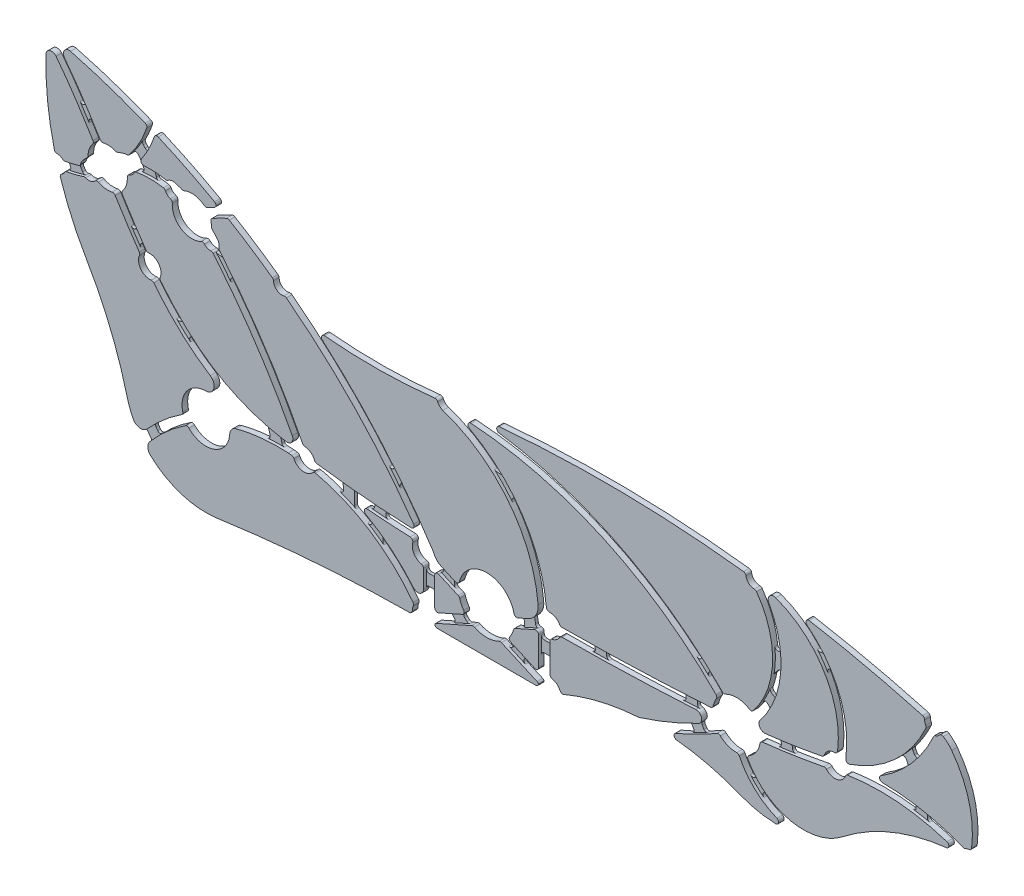
SolidWorks part; units mm, degrees
material "ｴﾎﾟｷｼ樹脂(充填剤なし)"
ref_plane "正面" through (0, 0, 0) normal (0, 0, 1) x (1, 0, 0)
ref_plane "平面" through (0, 0, 0) normal (0, 1, 0) x (1, 0, 0)
ref_plane "右側面" through (0, 0, 0) normal (1, 0, 0) x (0, 0, -1)
sketch "ｽｹｯﾁ1" plane through (0, 0, 0) normal (0, 0, 1) x (1, 0, 0)
  line L1 (22.5, 0.101) -> (22.5, -10.101)
  line L2 (22.5, 0.101) -> (22.5, -10.101)
  line L3 (-22.5, -6.4126) -> (-22.5, 0.101)
  line L4 (-22.5, -6.4126) -> (-22.5, 0.101)
  line L6 (11.119, 1.5832) -> (14.7807, 3.2107)
  line L7 (-17.0939, -10.9558) -> (-8.626, -7.1923)
  line L8 (-18.5, 0.042) -> (-18.5, -10.042)
  line L9 (-10.1663, -2.1231) -> (-17.0939, 0.9558)
  line L10 (-17.0939, -10.9558) -> (-8.626, -7.1923)
  line L11 (-18.5, 0.042) -> (-18.5, -10.042)
  line L12 (-10.1663, -2.1231) -> (-17.0939, 0.9558)
  line L13 (8.626, -7.1923) -> (17.0939, -10.9558)
  line L14 (17.0939, 0.9558) -> (10.1663, -2.1231)
  line L15 (18.5, -10.042) -> (18.5, 0.042)
  line L16 (8.626, -7.1923) -> (17.0939, -10.9558)
  line L17 (17.0939, 0.9558) -> (10.1663, -2.1231)
  line L18 (18.5, -10.042) -> (18.5, 0.042)
  line L19 (-16.2024, 3.8425) -> (-11.119, 1.5832)
  line L20 (11.119, 1.5832) -> (14.7807, 3.2107)
  line L21 (-16.2024, 3.8425) -> (-11.119, 1.5832)
  line L23 (-17.5, -16) -> (17.5, -16)
  line L24 (-5.2366, -8.9688) -> (-17.9339, -14.6121)
  line L25 (17.9339, -14.6121) -> (5.2366, -8.9688)
  line L26 (-17.5, -16) -> (17.5, -16)
  line L27 (-5.2366, -8.9688) -> (-17.9339, -14.6121)
  line L28 (17.9339, -14.6121) -> (5.2366, -8.9688)
  arc A26 (83.2113, 1.2758) -> (89.0603, -0.9998) centre (89, 7.5) ccw
  arc A27 (89.967, -1.5631) -> (89.0603, -0.9998) centre (89.0674, -1.9998) ccw
  arc A28 (89.967, -1.5631) -> (103.3566, -14.0607) centre (112.8701, 9.5532) ccw
  arc A29 (102.9573, -15.9879) -> (103.3566, -14.0607) centre (102.9829, -14.9883) ccw
  arc A30 (90.1176, -13.3365) -> (102.9573, -15.9879) centre (103.9017, 21) ccw
  arc A31 (90.1176, -13.3365) -> (67.6378, -7.8134) centre (59.3978, -89.8605) ccw
  arc A32 (67.3468, -5.898) -> (67.6378, -7.8134) centre (67.7378, -6.8184) ccw
  arc A33 (67.3468, -5.898) -> (82.0317, 1.4104) centre (13.9413, 119.818) ccw
  arc A34 (83.2113, 1.2758) -> (82.0317, 1.4104) centre (82.5302, 0.5435) ccw
  arc A35 (83.2113, 1.2758) -> (89.0603, -0.9998) centre (89, 7.5) ccw
  arc A36 (89.967, -1.5631) -> (89.0603, -0.9998) centre (89.0674, -1.9998) ccw
  arc A37 (89.967, -1.5631) -> (103.3566, -14.0607) centre (112.8701, 9.5532) ccw
  arc A38 (102.9573, -15.9879) -> (103.3566, -14.0607) centre (102.9829, -14.9883) ccw
  arc A39 (90.1176, -13.3365) -> (102.9573, -15.9879) centre (103.9017, 21) ccw
  arc A40 (90.1176, -13.3365) -> (67.6378, -7.8134) centre (59.3978, -89.8605) ccw
  arc A41 (67.3468, -5.898) -> (67.6378, -7.8134) centre (67.7378, -6.8184) ccw
  arc A42 (67.3468, -5.898) -> (82.0317, 1.4104) centre (13.9413, 119.818) ccw
  arc A43 (83.2113, 1.2758) -> (82.0317, 1.4104) centre (82.5302, 0.5435) ccw
  arc A45 (129.2172, 15.4989) -> (156.4002, 40.1644) centre (114.0417, 59.5347) ccw
  arc A46 (127.9008, 16.5808) -> (129.2172, 15.4989) centre (128.8914, 16.4443) ccw
  arc A47 (127.9008, 16.5808) -> (114.0595, 50.8962) centre (91.0356, 21.6602) ccw
  arc A48 (163.9203, 8.9775) -> (128.5572, 11.8079) centre (140.2604, -64.3004) ccw
  arc A49 (163.7257, 7.0322) -> (163.9203, 8.9775) centre (163.613, 8.0259) ccw
  arc A50 (163.7257, 7.0322) -> (126.7209, -8.1253) centre (172, -65.9175) ccw
  arc A51 (93.0844, -1.0722) -> (126.7209, -8.1253) centre (112.8701, 9.5532) ccw
  arc A52 (93.4427, 0.2535) -> (93.0844, -1.0722) centre (93.9654, -0.5991) ccw
  arc A53 (93.4427, 0.2535) -> (97.3718, 6.0294) centre (89, 7.5) ccw
  arc A54 (98.2474, 6.8503) -> (97.3718, 6.0294) centre (98.3567, 5.8563) ccw
  arc A55 (98.2474, 6.8503) -> (120.0633, 10.1693) centre (69.0994, 271.8045) ccw
  arc A56 (121.0036, 9.8502) -> (120.0633, 10.1693) centre (120.2545, 9.1877) ccw
  arc A57 (121.0036, 9.8502) -> (127.7673, 11.1556) centre (124, 12.5) ccw
  arc A58 (128.5572, 11.8079) -> (127.7673, 11.1556) centre (128.7091, 10.8195) ccw
  arc A59 (163.9203, 8.9775) -> (128.5572, 11.8079) centre (140.2604, -64.3004) ccw
  arc A60 (163.7257, 7.0322) -> (163.9203, 8.9775) centre (163.613, 8.0259) ccw
  arc A61 (163.7257, 7.0322) -> (126.7209, -8.1253) centre (172, -65.9175) ccw
  arc A62 (93.0844, -1.0722) -> (126.7209, -8.1253) centre (112.8701, 9.5532) ccw
  arc A63 (93.4427, 0.2535) -> (93.0844, -1.0722) centre (93.9654, -0.5991) ccw
  arc A64 (93.4427, 0.2535) -> (97.3718, 6.0294) centre (89, 7.5) ccw
  arc A65 (98.2474, 6.8503) -> (97.3718, 6.0294) centre (98.3567, 5.8563) ccw
  arc A66 (98.2474, 6.8503) -> (120.0633, 10.1693) centre (69.0994, 271.8045) ccw
  arc A67 (121.0036, 9.8502) -> (120.0633, 10.1693) centre (120.2545, 9.1877) ccw
  arc A68 (121.0036, 9.8502) -> (127.7673, 11.1556) centre (124, 12.5) ccw
  arc A69 (128.5572, 11.8079) -> (127.7673, 11.1556) centre (128.7091, 10.8195) ccw
  arc A70 (114.85, 52.6669) -> (114.0595, 50.8962) centre (114.6782, 51.6818) ccw
  arc A71 (155.2686, 43.5545) -> (114.85, 52.6669) centre (42.29, -363.3692) ccw
  arc A72 (156.0008, 42.5682) -> (155.2686, 43.5545) centre (155.001, 42.5909) ccw
  arc A73 (156.0008, 42.5682) -> (156.3681, 41.0602) centre (159, 42.5) ccw
  arc A74 (156.4002, 40.1644) -> (156.3681, 41.0602) centre (155.4908, 40.5803) ccw
  arc A75 (129.2172, 15.4989) -> (156.4002, 40.1644) centre (114.0417, 59.5347) ccw
  arc A76 (127.9008, 16.5808) -> (129.2172, 15.4989) centre (128.8914, 16.4443) ccw
  arc A77 (127.9008, 16.5808) -> (114.0595, 50.8962) centre (91.0356, 21.6602) ccw
  arc A78 (114.85, 52.6669) -> (114.0595, 50.8962) centre (114.6782, 51.6818) ccw
  arc A79 (155.2686, 43.5545) -> (114.85, 52.6669) centre (42.29, -363.3692) ccw
  arc A80 (156.0008, 42.5682) -> (155.2686, 43.5545) centre (155.001, 42.5909) ccw
  arc A81 (156.0008, 42.5682) -> (156.3681, 41.0602) centre (159, 42.5) ccw
  arc A82 (156.4002, 40.1644) -> (156.3681, 41.0602) centre (155.4908, 40.5803) ccw
  arc A83 (97.4246, 13.2154) -> (99.214, 9.978) centre (98.9855, 11.9649) ccw
  arc A84 (97.4246, 13.2154) -> (100.5051, 50.879) centre (71.0713, 34.3286) ccw
  arc A85 (93.5868, 14.6562) -> (85.0963, 15.0506) centre (89, 7.5) ccw
  arc A86 (171.786, 10.4924) -> (170.5639, 10.1339) centre (172, 7.5) ccw
  arc A87 (169.717, 10.0822) -> (170.5639, 10.1339) centre (170.0852, 11.0119) ccw
  arc A88 (169.717, 10.0822) -> (140.9263, 15.6997) centre (140.2604, -64.3004) ccw
  arc A89 (140.4029, 17.5466) -> (140.9263, 15.6997) centre (140.9346, 16.6997) ccw
  arc A90 (140.4029, 17.5466) -> (159.198, 39.0695) centre (114.0417, 59.5347) ccw
  arc A91 (159.8316, 39.6176) -> (159.198, 39.0695) centre (160.1088, 38.6568) ccw
  arc A92 (159.8316, 39.6176) -> (161.317, 40.5944) centre (159, 42.5) ccw
  arc A93 (162.6526, 40.7855) -> (161.317, 40.5944) centre (162.0894, 39.9592) ccw
  arc A94 (165.6353, 37.9447) -> (162.6526, 40.7855) centre (155.4945, 30.2837) ccw
  arc A95 (172.7066, 11.3632) -> (165.6353, 37.9447) centre (136.5587, 15.9784) ccw
  arc A96 (171.786, 10.4924) -> (172.7066, 11.3632) centre (171.7146, 11.4898) ccw
  arc A97 (171.786, 10.4924) -> (170.5639, 10.1339) centre (172, 7.5) ccw
  arc A98 (169.717, 10.0822) -> (170.5639, 10.1339) centre (170.0852, 11.0119) ccw
  arc A99 (169.717, 10.0822) -> (140.9263, 15.6997) centre (140.2604, -64.3004) ccw
  arc A100 (140.4029, 17.5466) -> (140.9263, 15.6997) centre (140.9346, 16.6997) ccw
  arc A101 (140.4029, 17.5466) -> (159.198, 39.0695) centre (114.0417, 59.5347) ccw
  arc A102 (159.8316, 39.6176) -> (159.198, 39.0695) centre (160.1088, 38.6568) ccw
  arc A103 (159.8316, 39.6176) -> (161.317, 40.5944) centre (159, 42.5) ccw
  arc A104 (162.6526, 40.7855) -> (161.317, 40.5944) centre (162.0894, 39.9592) ccw
  arc A105 (165.6353, 37.9447) -> (162.6526, 40.7855) centre (155.4945, 30.2837) ccw
  arc A106 (172.7066, 11.3632) -> (165.6353, 37.9447) centre (136.5587, 15.9784) ccw
  arc A107 (171.786, 10.4924) -> (172.7066, 11.3632) centre (171.7146, 11.4898) ccw
  arc A108 (83.9236, 15.238) -> (85.0963, 15.0506) centre (84.637, 15.9389) ccw
  arc A109 (83.9236, 15.238) -> (4.4224, 55.2639) centre (-14.6672, -81.6202) ccw
  arc A110 (4.471, 57.2503) -> (4.4224, 55.2639) centre (4.5606, 56.2543) ccw
  arc A111 (91.4838, 56.0721) -> (4.471, 57.2503) centre (42.29, -363.3692) ccw
  arc A112 (92.3587, 55.2099) -> (91.4838, 56.0721) centre (91.3673, 55.0789) ccw
  arc A113 (92.3587, 55.2099) -> (95.319, 52.6028) centre (95.3328, 55.6027) ccw
  arc A114 (96.1287, 52.1831) -> (95.319, 52.6028) centre (95.3143, 51.6028) ccw
  arc A115 (94.9009, 14.8656) -> (96.1287, 52.1831) centre (71.0713, 34.3286) ccw
  arc A116 (93.5868, 14.6562) -> (94.9009, 14.8656) centre (94.1264, 15.4981) ccw
  arc A117 (93.5868, 14.6562) -> (85.0963, 15.0506) centre (89, 7.5) ccw
  arc A118 (83.9236, 15.238) -> (85.0963, 15.0506) centre (84.637, 15.9389) ccw
  arc A119 (83.9236, 15.238) -> (4.4224, 55.2639) centre (-14.6672, -81.6202) ccw
  arc A120 (4.471, 57.2503) -> (4.4224, 55.2639) centre (4.5606, 56.2543) ccw
  arc A121 (91.4838, 56.0721) -> (4.471, 57.2503) centre (42.29, -363.3692) ccw
  arc A122 (92.3587, 55.2099) -> (91.4838, 56.0721) centre (91.3673, 55.0789) ccw
  arc A123 (92.3587, 55.2099) -> (95.319, 52.6028) centre (95.3328, 55.6027) ccw
  arc A124 (96.1287, 52.1831) -> (95.319, 52.6028) centre (95.3143, 51.6028) ccw
  arc A125 (94.9009, 14.8656) -> (96.1287, 52.1831) centre (71.0713, 34.3286) ccw
  arc A126 (93.5868, 14.6562) -> (94.9009, 14.8656) centre (94.1264, 15.4981) ccw
  arc A127 (81.6673, 13.2539) -> (-5.6096, 53.2849) centre (-14.6672, -81.6202) ccw
  arc A128 (81.8017, 12.0204) -> (81.6673, 13.2539) centre (80.9548, 12.5522) ccw
  arc A129 (81.8017, 12.0204) -> (80.6633, 9.158) centre (89, 7.5) ccw
  arc A130 (79.7472, 8.3552) -> (80.6633, 9.158) centre (79.6825, 9.3531) ccw
  arc A131 (26.8289, 6.5106) -> (79.7472, 8.3552) centre (22.5, 890.7) ccw
  arc A132 (25.9592, 7.0085) -> (26.8289, 6.5106) centre (26.824, 7.5106) ccw
  arc A133 (25.9592, 7.0085) -> (22.314, 8.9957) centre (22.5, 5) ccw
  arc A134 (21.2718, 9.9017) -> (22.314, 8.9957) centre (22.2675, 9.9946) ccw
  arc A135 (21.2718, 9.9017) -> (-6.1525, 51.4076) centre (-31.2679, 5) ccw
  arc A136 (-5.6096, 53.2849) -> (-6.1525, 51.4076) centre (-5.6766, 52.2871) ccw
  arc A137 (81.6673, 13.2539) -> (-5.6096, 53.2849) centre (-14.6672, -81.6202) ccw
  arc A138 (81.8017, 12.0204) -> (81.6673, 13.2539) centre (80.9548, 12.5522) ccw
  arc A139 (81.8017, 12.0204) -> (80.6633, 9.158) centre (89, 7.5) ccw
  arc A140 (79.7472, 8.3552) -> (80.6633, 9.158) centre (79.6825, 9.3531) ccw
  arc A141 (26.8289, 6.5106) -> (79.7472, 8.3552) centre (22.5, 890.7) ccw
  arc A142 (25.9592, 7.0085) -> (26.8289, 6.5106) centre (26.824, 7.5106) ccw
  arc A143 (25.9592, 7.0085) -> (22.314, 8.9957) centre (22.5, 5) ccw
  arc A144 (21.2718, 9.9017) -> (22.314, 8.9957) centre (22.2675, 9.9946) ccw
  arc A145 (21.2718, 9.9017) -> (-6.1525, 51.4076) centre (-31.2679, 5) ccw
  arc A146 (-5.6096, 53.2849) -> (-6.1525, 51.4076) centre (-5.6766, 52.2871) ccw
  arc A147 (102.9446, 53.7342) -> (100.5051, 50.879) centre (102.2484, 51.8592) ccw
  arc A148 (23.3, 1.0808) -> (25.969, 3.0085) centre (22.5, 5) ccw
  arc A149 (26.8313, 3.5106) -> (25.969, 3.0085) centre (26.8362, 2.5106) ccw
  arc A150 (26.8313, 3.5106) -> (74.4485, 5.0222) centre (22.5, 890.7) ccw
  arc A151 (75.487, 1.2505) -> (74.4485, 5.0222) centre (74.5656, 3.0256) ccw
  arc A152 (54.3014, -7.5287) -> (75.487, 1.2505) centre (13.9413, 119.818) ccw
  arc A153 (54.0639, -7.5734) -> (54.3014, -7.5287) centre (53.9993, -6.5755) ccw
  arc A154 (54.0639, -7.5734) -> (27.4366, -13.8466) centre (59.3978, -89.8605) ccw
  arc A155 (26.1392, -13.3399) -> (27.4366, -13.8466) centre (27.049, -12.9248) ccw
  arc A156 (26.1392, -13.3399) -> (23.3, -11.0808) centre (22.5, -15) ccw
  arc A157 (22.5, -10.101) -> (23.3, -11.0808) centre (23.5, -10.101) ccw
  arc A158 (23.3, 1.0808) -> (22.5, 0.101) centre (23.5, 0.101) ccw
  arc A159 (23.3, 1.0808) -> (25.969, 3.0085) centre (22.5, 5) ccw
  arc A160 (26.8313, 3.5106) -> (25.969, 3.0085) centre (26.8362, 2.5106) ccw
  arc A161 (26.8313, 3.5106) -> (74.4485, 5.0222) centre (22.5, 890.7) ccw
  arc A162 (75.487, 1.2505) -> (74.4485, 5.0222) centre (74.5656, 3.0256) ccw
  arc A163 (54.3014, -7.5287) -> (75.487, 1.2505) centre (13.9413, 119.818) ccw
  arc A164 (54.0639, -7.5734) -> (54.3014, -7.5287) centre (53.9993, -6.5755) ccw
  arc A165 (54.0639, -7.5734) -> (27.4366, -13.8466) centre (59.3978, -89.8605) ccw
  arc A166 (26.1392, -13.3399) -> (27.4366, -13.8466) centre (27.049, -12.9248) ccw
  arc A167 (26.1392, -13.3399) -> (23.3, -11.0808) centre (22.5, -15) ccw
  arc A168 (22.5, -10.101) -> (23.3, -11.0808) centre (23.5, -10.101) ccw
  arc A169 (23.3, 1.0808) -> (22.5, 0.101) centre (23.5, 0.101) ccw
  arc A170 (124.9796, 17.3747) -> (102.9446, 53.7342) centre (91.0356, 21.6602) ccw
  arc A171 (123.99, 16.5) -> (124.9796, 17.3747) centre (123.9875, 17.5) ccw
  arc A172 (123.99, 16.5) -> (120.207, 13.7702) centre (124, 12.5) ccw
  arc A179 (119.4498, 13.1062) -> (120.207, 13.7702) centre (119.2588, 14.0878) ccw
  arc A180 (99.214, 9.978) -> (119.4498, 13.1062) centre (69.0994, 271.8045) ccw
  arc A181 (97.4246, 13.2154) -> (99.214, 9.978) centre (98.9855, 11.9649) ccw
  arc A182 (97.4246, 13.2154) -> (100.5051, 50.879) centre (71.0713, 34.3286) ccw
  arc A183 (102.9446, 53.7342) -> (100.5051, 50.879) centre (102.2484, 51.8592) ccw
  arc A184 (124.9796, 17.3747) -> (102.9446, 53.7342) centre (91.0356, 21.6602) ccw
  arc A185 (123.99, 16.5) -> (124.9796, 17.3747) centre (123.9875, 17.5) ccw
  arc A186 (123.99, 16.5) -> (120.207, 13.7702) centre (124, 12.5) ccw
  arc A187 (119.4498, 13.1062) -> (120.207, 13.7702) centre (119.2588, 14.0878) ccw
  arc A188 (99.214, 9.978) -> (119.4498, 13.1062) centre (69.0994, 271.8045) ccw
  arc A196 (-9.6113, -2.7608) -> (-8.2111, -5.7077) centre (0, 0) ccw
  arc A197 (-8.626, -7.1923) -> (-8.2111, -5.7077) centre (-9.0322, -6.2785) ccw
  arc A198 (-26.3403, 6.1191) -> (-23.3, 1.0808) centre (-22.5, 5) ccw
  arc A199 (-22.5, 0.101) -> (-23.3, 1.0808) centre (-23.5, 0.101) ccw
  arc A200 (-26.0294, -7.7013) -> (-22.5, -6.4126) centre (-24.5, -6.4126) ccw
  arc A201 (-150.204, 61.7869) -> (-145.3266, 62.9598) centre (-156.5, 98.6967) ccw
  arc A202 (-151.0229, 62.0134) -> (-150.204, 61.7869) centre (-150.3722, 62.7727) ccw
  arc A203 (-151.0229, 62.0134) -> (-152.9962, 62.7355) centre (-152.9752, 59.7355) ccw
  arc A204 (-153.9743, 63.4967) -> (-152.9962, 62.7355) centre (-153.0032, 63.7354) ccw
  arc A205 (-156.9587, 91.4184) -> (-153.9743, 63.4967) centre (-52.35, 88.479) ccw
  arc A206 (-153.3843, 92.5946) -> (-156.9587, 91.4184) centre (-154.9595, 91.3622) ccw
  arc A207 (-140.3274, 72.022) -> (-140.2368, 73.1947) centre (-141.0885, 72.6707) ccw
  arc A208 (-92.6465, 72.9722) -> (-97.7506, 70.3671) centre (-65, 12.5) ccw
  arc A209 (-91.7165, 72.9204) -> (-92.6465, 72.9722) centre (-92.2307, 72.0627) ccw
  arc A210 (-76.3493, 62.7985) -> (-91.7165, 72.9204) centre (-203.2901, -113.1988) ccw
  arc A211 (-75.9352, 62.0305) -> (-76.3493, 62.7985) centre (-76.9343, 61.9874) ccw
  arc A212 (-75.9352, 62.0305) -> (-72.1979, 59.2524) centre (-72.938, 62.1596) ccw
  arc A213 (-71.3431, 59.0772) -> (-72.1979, 59.2524) centre (-71.9512, 58.2833) ccw
  arc A214 (-26.022, 11.9612) -> (-71.3431, 59.0772) centre (-203.2901, -113.1988) ccw
  arc A215 (-26.8783, 10.3852) -> (-26.022, 11.9612) centre (-26.8389, 11.3844) ccw
  arc A216 (-60.4936, 13.364) -> (-26.8783, 10.3852) centre (-13.2682, 355.1295) ccw
  arc A217 (-61.2853, 13.9837) -> (-60.4936, 13.364) centre (-60.3567, 14.3546) ccw
  arc A218 (-61.2853, 13.9837) -> (-64.7539, 16.4924) centre (-65, 12.5) ccw
  arc A219 (-65.5834, 17.0366) -> (-64.7539, 16.4924) centre (-64.6924, 17.4905) ccw
  arc A220 (-65.5834, 17.0366) -> (-95.1344, 61.7139) centre (-276.8279, -90.5756) ccw
  arc A221 (-95.3497, 62.5466) -> (-95.1344, 61.7139) centre (-94.368, 62.3562) ccw
  arc A222 (-95.3497, 62.5466) -> (-96.0213, 65.0748) centre (-98.2949, 63.1176) ccw
  arc A223 (-96.0213, 65.0748) -> (-97.7054, 66.8832) centre (-120, 44.4324) ccw
  arc A224 (-98.0007, 67.5789) -> (-97.7054, 66.8832) centre (-97.0008, 67.5928) ccw
  arc A225 (-98.0007, 67.5789) -> (-98.2258, 69.2449) centre (-105, 67.4812) ccw
  arc A226 (-97.7506, 70.3671) -> (-98.2258, 69.2449) centre (-97.2581, 69.4969) ccw
  arc A227 (-92.6465, 72.9722) -> (-97.7506, 70.3671) centre (-65, 12.5) ccw
  arc A228 (-91.7165, 72.9204) -> (-92.6465, 72.9722) centre (-92.2307, 72.0627) ccw
  arc A229 (-76.3493, 62.7985) -> (-91.7165, 72.9204) centre (-203.2901, -113.1988) ccw
  arc A230 (-75.9352, 62.0305) -> (-76.3493, 62.7985) centre (-76.9343, 61.9874) ccw
  arc A231 (-75.9352, 62.0305) -> (-72.1979, 59.2524) centre (-72.938, 62.1596) ccw
  arc A232 (-71.3431, 59.0772) -> (-72.1979, 59.2524) centre (-71.9512, 58.2833) ccw
  arc A233 (-26.022, 11.9612) -> (-71.3431, 59.0772) centre (-203.2901, -113.1988) ccw
  arc A234 (-26.8783, 10.3852) -> (-26.022, 11.9612) centre (-26.8389, 11.3844) ccw
  arc A235 (-60.4936, 13.364) -> (-26.8783, 10.3852) centre (-13.2682, 355.1295) ccw
  arc A236 (-61.2853, 13.9837) -> (-60.4936, 13.364) centre (-60.3567, 14.3546) ccw
  arc A237 (-61.2853, 13.9837) -> (-64.7539, 16.4924) centre (-65, 12.5) ccw
  arc A238 (-65.5834, 17.0366) -> (-64.7539, 16.4924) centre (-64.6924, 17.4905) ccw
  arc A239 (-65.5834, 17.0366) -> (-95.1344, 61.7139) centre (-276.8279, -90.5756) ccw
  arc A240 (-95.3497, 62.5466) -> (-95.1344, 61.7139) centre (-94.368, 62.3562) ccw
  arc A241 (-95.3497, 62.5466) -> (-96.0213, 65.0748) centre (-98.2949, 63.1176) ccw
  arc A242 (-96.0213, 65.0748) -> (-97.7054, 66.8832) centre (-120, 44.4324) ccw
  arc A243 (-98.0007, 67.5789) -> (-97.7054, 66.8832) centre (-97.0008, 67.5928) ccw
  arc A244 (-98.0007, 67.5789) -> (-98.2258, 69.2449) centre (-105, 67.4812) ccw
  arc A245 (-97.7506, 70.3671) -> (-98.2258, 69.2449) centre (-97.2581, 69.4969) ccw
  arc A246 (-140.3274, 72.022) -> (-141.9993, 67.5789) centre (-135, 67.4812) ccw
  arc A247 (-142.2946, 66.8832) -> (-141.9993, 67.5789) centre (-142.9992, 67.5928) ccw
  arc A248 (-142.2946, 66.8832) -> (-143.9787, 65.0748) centre (-120, 44.4324) ccw
  arc A249 (-143.9787, 65.0748) -> (-144.645, 63.7151) centre (-141.7051, 63.1176) ccw
  arc A250 (-145.3266, 62.9598) -> (-144.645, 63.7151) centre (-145.625, 63.9142) ccw
  arc A251 (-150.204, 61.7869) -> (-145.3266, 62.9598) centre (-156.5, 98.6967) ccw
  arc A252 (-151.0229, 62.0134) -> (-150.204, 61.7869) centre (-150.3722, 62.7727) ccw
  arc A253 (-151.0229, 62.0134) -> (-152.9962, 62.7355) centre (-152.9752, 59.7355) ccw
  arc A254 (-153.9743, 63.4967) -> (-152.9962, 62.7355) centre (-153.0032, 63.7354) ccw
  arc A255 (-156.9587, 91.4184) -> (-153.9743, 63.4967) centre (-52.35, 88.479) ccw
  arc A256 (-153.3843, 92.5946) -> (-156.9587, 91.4184) centre (-154.9595, 91.3622) ccw
  arc A257 (-140.3274, 72.022) -> (-140.2368, 73.1947) centre (-141.0885, 72.6707) ccw
  arc A258 (-140.3274, 72.022) -> (-141.9993, 67.5789) centre (-135, 67.4812) ccw
  arc A259 (-142.2946, 66.8832) -> (-141.9993, 67.5789) centre (-142.9992, 67.5928) ccw
  arc A260 (-142.2946, 66.8832) -> (-143.9787, 65.0748) centre (-120, 44.4324) ccw
  arc A261 (-143.9787, 65.0748) -> (-144.645, 63.7151) centre (-141.7051, 63.1176) ccw
  arc A262 (-145.3266, 62.9598) -> (-144.645, 63.7151) centre (-145.625, 63.9142) ccw
  arc A263 (-26.0294, -7.7013) -> (-43.0938, 6.4818) centre (-74.1755, -48.2713) ccw
  arc A264 (-42.5161, 8.3479) -> (-43.0938, 6.4818) centre (-42.6001, 7.3514) ccw
  arc A265 (-42.5161, 8.3479) -> (-27.2601, 7.398) centre (-13.2682, 355.1295) ccw
  arc A266 (-122.9876, 76.0572) -> (-118.3344, 85.3171) centre (-156.5, 98.6967) ccw
  arc A267 (-116.993, 85.9037) -> (-118.3344, 85.3171) centre (-117.3907, 84.9862) ccw
  arc A268 (-96.9469, 75.9576) -> (-116.993, 85.9037) centre (-203.2901, -113.1988) ccw
  arc A269 (-96.9768, 74.198) -> (-96.9469, 75.9576) centre (-97.4369, 75.0859) ccw
  arc A270 (-96.9768, 74.198) -> (-99.4771, 72.8365) centre (-65, 12.5) ccw
  arc A271 (-100.6016, 72.9268) -> (-99.4771, 72.8365) centre (-99.9733, 73.7047) ccw
  arc A272 (-100.6016, 72.9268) -> (-107.7452, 73.9205) centre (-105, 67.4812) ccw
  arc A273 (-108.5008, 73.9088) -> (-107.7452, 73.9205) centre (-108.1373, 74.8404) ccw
  arc A274 (-108.5008, 73.9088) -> (-110.8362, 74.7163) centre (-120, 44.4324) ccw
  arc A275 (-110.8362, 74.7163) -> (-113.5331, 74.2236) centre (-111.7051, 71.8449) ccw
  arc A276 (-114.3306, 74.0344) -> (-113.5331, 74.2236) centre (-114.1425, 75.0165) ccw
  arc A277 (-114.3306, 74.0344) -> (-122.0896, 74.4999) centre (-120, 44.4324) ccw
  arc A278 (-122.9876, 76.0572) -> (-122.0896, 74.4999) centre (-122.1589, 75.4974) ccw
  arc A279 (-122.9876, 76.0572) -> (-118.3344, 85.3171) centre (-156.5, 98.6967) ccw
  arc A280 (-116.993, 85.9037) -> (-118.3344, 85.3171) centre (-117.3907, 84.9862) ccw
  arc A281 (-96.9469, 75.9576) -> (-116.993, 85.9037) centre (-203.2901, -113.1988) ccw
  arc A282 (-96.9768, 74.198) -> (-96.9469, 75.9576) centre (-97.4369, 75.0859) ccw
  arc A283 (-96.9768, 74.198) -> (-99.4771, 72.8365) centre (-65, 12.5) ccw
  arc A284 (-100.6016, 72.9268) -> (-99.4771, 72.8365) centre (-99.9733, 73.7047) ccw
  arc A285 (-100.6016, 72.9268) -> (-107.7452, 73.9205) centre (-105, 67.4812) ccw
  arc A286 (-108.5008, 73.9088) -> (-107.7452, 73.9205) centre (-108.1373, 74.8404) ccw
  arc A287 (-108.5008, 73.9088) -> (-110.8362, 74.7163) centre (-120, 44.4324) ccw
  arc A288 (-110.8362, 74.7163) -> (-113.5331, 74.2236) centre (-111.7051, 71.8449) ccw
  arc A289 (-114.3306, 74.0344) -> (-113.5331, 74.2236) centre (-114.1425, 75.0165) ccw
  arc A290 (-114.3306, 74.0344) -> (-122.0896, 74.4999) centre (-120, 44.4324) ccw
  arc A291 (-122.9876, 76.0572) -> (-122.0896, 74.4999) centre (-122.1589, 75.4974) ccw
  arc A292 (-26.3403, 6.1191) -> (-27.2601, 7.398) centre (-27.3003, 6.3988) ccw
  arc A293 (-26.3403, 6.1191) -> (-23.3, 1.0808) centre (-22.5, 5) ccw
  arc A294 (-22.5, 0.101) -> (-23.3, 1.0808) centre (-23.5, 0.101) ccw
  arc A295 (-26.0294, -7.7013) -> (-22.5, -6.4126) centre (-24.5, -6.4126) ccw
  arc A296 (-106.0705, 1.5503) -> (-91.5134, 7.0221) centre (-100, 7.5) ccw
  arc A297 (-89.2736, 9.7568) -> (-91.5134, 7.0221) centre (-88.5182, 6.8535) ccw
  arc A298 (-70.6824, 11.5869) -> (-89.2736, 9.7568) centre (-74.1755, -48.2713) ccw
  arc A299 (-70.604, 11.5793) -> (-70.6824, 11.5869) centre (-70.7407, 10.5886) ccw
  arc A300 (-70.604, 11.5793) -> (-69.4305, 11.426) centre (-59.3082, 93.4746) ccw
  arc A301 (-68.6424, 10.8468) -> (-69.4305, 11.426) centre (-69.553, 10.4335) ccw
  arc A302 (-68.6424, 10.8468) -> (-61.9641, 9.8955) centre (-65, 12.5) ccw
  arc A303 (-60.9851, 10.2199) -> (-61.9641, 9.8955) centre (-61.2051, 9.2444) ccw
  arc A304 (-26.225, -12.2719) -> (-60.9851, 10.2199) centre (-74.1755, -48.2713) ccw
  arc A305 (-26.1198, -13.2978) -> (-26.225, -12.2719) centre (-27.0247, -12.8723) ccw
  arc A306 (-26.1198, -13.2978) -> (-26.5, -15.0192) centre (-22.5, -15) ccw
  arc A307 (-27.4903, -16.024) -> (-26.5, -15.0192) centre (-27.4999, -15.024) ccw
  arc A308 (-27.4903, -16.024) -> (-95.9045, -21.2094) centre (-22.5, -535.7727) ccw
  arc A309 (-119.7512, -13.7341) -> (-95.9045, -21.2094) centre (-100, 7.5) ccw
  arc A310 (-120.0008, -9.6028) -> (-119.7512, -13.7341) centre (-117.708, -11.5375) ccw
  arc A311 (-107.3377, 1.6835) -> (-120.0008, -9.6028) centre (-74.1755, -48.2713) ccw
  arc A312 (-106.0705, 1.5503) -> (-107.3377, 1.6835) centre (-106.7847, 0.8503) ccw
  arc A313 (-106.0705, 1.5503) -> (-91.5134, 7.0221) centre (-100, 7.5) ccw
  arc A314 (-89.2736, 9.7568) -> (-91.5134, 7.0221) centre (-88.5182, 6.8535) ccw
  arc A315 (-70.6824, 11.5869) -> (-89.2736, 9.7568) centre (-74.1755, -48.2713) ccw
  arc A316 (-70.604, 11.5793) -> (-70.6824, 11.5869) centre (-70.7407, 10.5886) ccw
  arc A317 (-70.604, 11.5793) -> (-69.4305, 11.426) centre (-59.3082, 93.4746) ccw
  arc A318 (-68.6424, 10.8468) -> (-69.4305, 11.426) centre (-69.553, 10.4335) ccw
  arc A319 (-68.6424, 10.8468) -> (-61.9641, 9.8955) centre (-65, 12.5) ccw
  arc A320 (-60.9851, 10.2199) -> (-61.9641, 9.8955) centre (-61.2051, 9.2444) ccw
  arc A321 (-26.225, -12.2719) -> (-60.9851, 10.2199) centre (-74.1755, -48.2713) ccw
  arc A322 (-26.1198, -13.2978) -> (-26.225, -12.2719) centre (-27.0247, -12.8723) ccw
  arc A323 (-26.1198, -13.2978) -> (-26.5, -15.0192) centre (-22.5, -15) ccw
  arc A324 (-27.4903, -16.024) -> (-26.5, -15.0192) centre (-27.4999, -15.024) ccw
  arc A325 (-27.4903, -16.024) -> (-95.9045, -21.2094) centre (-22.5, -535.7727) ccw
  arc A326 (-119.7512, -13.7341) -> (-95.9045, -21.2094) centre (-100, 7.5) ccw
  arc A327 (-120.0008, -9.6028) -> (-119.7512, -13.7341) centre (-117.708, -11.5375) ccw
  arc A328 (-107.3377, 1.6835) -> (-120.0008, -9.6028) centre (-74.1755, -48.2713) ccw
  arc A329 (-106.0705, 1.5503) -> (-107.3377, 1.6835) centre (-106.7847, 0.8503) ccw
  arc A330 (-26.0294, -7.7013) -> (-43.0938, 6.4818) centre (-74.1755, -48.2713) ccw
  arc A331 (-42.5161, 8.3479) -> (-43.0938, 6.4818) centre (-42.6001, 7.3514) ccw
  arc A332 (-42.5161, 8.3479) -> (-27.2601, 7.398) centre (-13.2682, 355.1295) ccw
  arc A333 (-26.3403, 6.1191) -> (-27.2601, 7.398) centre (-27.3003, 6.3988) ccw
  arc A334 (-18.5, -10.042) -> (-17.0939, -10.9558) centre (-17.5, -10.042) ccw
  arc A335 (-17.0939, 0.9558) -> (-18.5, 0.042) centre (-17.5, 0.042) ccw
  arc A336 (-9.6113, -2.7608) -> (-10.1663, -2.1231) centre (-10.5725, -3.0369) ccw
  arc A337 (-148.2331, 96.7006) -> (-150.3263, 93.5472) centre (-148.7406, 94.766) ccw
  arc A338 (-121.6343, 87.8518) -> (-148.2331, 96.7006) centre (-203.2901, -113.1988) ccw
  arc A339 (-121.0642, 86.6023) -> (-121.6343, 87.8518) centre (-122.0106, 86.9253) ccw
  arc A340 (-127.3364, 75.2137) -> (-121.0642, 86.6023) centre (-156.5, 98.6967) ccw
  arc A341 (-128.1602, 74.8418) -> (-127.3364, 75.2137) centre (-128.1152, 75.8408) ccw
  arc A342 (-128.1602, 74.8418) -> (-129.1638, 74.7163) centre (-128.2949, 71.8449) ccw
  arc A343 (-129.1638, 74.7163) -> (-131.4992, 73.9088) centre (-120, 44.4324) ccw
  arc A344 (-132.2548, 73.9205) -> (-131.4992, 73.9088) centre (-131.8627, 74.8404) ccw
  arc A345 (-100.5079, 61.0921) -> (-98.2079, 60.1189) centre (-98.2949, 63.1176) ccw
  arc A346 (-97.4124, 59.7615) -> (-98.2079, 60.1189) centre (-98.1789, 59.1193) ccw
  arc A347 (-69.2577, 17.6177) -> (-97.4124, 59.7615) centre (-276.8279, -90.5756) ccw
  arc A348 (-71.3333, 14.7162) -> (-69.2577, 17.6177) centre (-71.0313, 16.6932) ccw
  arc A349 (-116.299, 42.915) -> (-116.1539, 41.9101) centre (-115.3737, 42.5356) ccw
  arc A350 (-116.299, 42.915) -> (-120.4118, 48.4111) centre (-120, 44.4324) ccw
  arc A351 (-121.3328, 48.8307) -> (-120.4118, 48.4111) centre (-120.5147, 49.4058) ccw
  arc A352 (-129.6706, 62.9428) -> (-129.7605, 61.7697) centre (-128.9093, 62.2944) ccw
  arc A353 (-129.6706, 62.9428) -> (-128.0179, 67.9818) centre (-135, 67.4812) ccw
  arc A354 (-127.3391, 69.0012) -> (-128.0179, 67.9818) centre (-127.0205, 68.0533) ccw
  arc A355 (-127.3391, 69.0012) -> (-125.5769, 70.575) centre (-128.2949, 71.8449) ccw
  arc A356 (-124.8496, 71.1356) -> (-125.5769, 70.575) centre (-124.6709, 70.1517) ccw
  arc A357 (-115.1504, 71.1356) -> (-124.8496, 71.1356) centre (-120, 44.4324) ccw
  arc A358 (-114.4231, 70.575) -> (-115.1504, 71.1356) centre (-115.3291, 70.1517) ccw
  arc A359 (-114.4231, 70.575) -> (-112.6609, 69.0012) centre (-111.7051, 71.8449) ccw
  arc A360 (-111.9821, 67.9818) -> (-112.6609, 69.0012) centre (-112.9795, 68.0533) ccw
  arc A361 (-111.9821, 67.9818) -> (-101.7149, 61.3) centre (-105, 67.4812) ccw
  arc A362 (-100.5079, 61.0921) -> (-101.7149, 61.3) centre (-101.2456, 60.4169) ccw
  arc A363 (-100.5079, 61.0921) -> (-98.2079, 60.1189) centre (-98.2949, 63.1176) ccw
  arc A364 (-97.4124, 59.7615) -> (-98.2079, 60.1189) centre (-98.1789, 59.1193) ccw
  arc A365 (-69.2577, 17.6177) -> (-97.4124, 59.7615) centre (-276.8279, -90.5756) ccw
  arc A366 (-71.3333, 14.7162) -> (-69.2577, 17.6177) centre (-71.0313, 16.6932) ccw
  arc A367 (-116.299, 42.915) -> (-116.1539, 41.9101) centre (-115.3737, 42.5356) ccw
  arc A368 (-116.299, 42.915) -> (-120.4118, 48.4111) centre (-120, 44.4324) ccw
  arc A369 (-121.3328, 48.8307) -> (-120.4118, 48.4111) centre (-120.5147, 49.4058) ccw
  arc A370 (-129.6706, 62.9428) -> (-129.7605, 61.7697) centre (-128.9093, 62.2944) ccw
  arc A371 (-129.6706, 62.9428) -> (-128.0179, 67.9818) centre (-135, 67.4812) ccw
  arc A372 (-127.3391, 69.0012) -> (-128.0179, 67.9818) centre (-127.0205, 68.0533) ccw
  arc A373 (-127.3391, 69.0012) -> (-125.5769, 70.575) centre (-128.2949, 71.8449) ccw
  arc A374 (-124.8496, 71.1356) -> (-125.5769, 70.575) centre (-124.6709, 70.1517) ccw
  arc A375 (-115.1504, 71.1356) -> (-124.8496, 71.1356) centre (-120, 44.4324) ccw
  arc A376 (-114.4231, 70.575) -> (-115.1504, 71.1356) centre (-115.3291, 70.1517) ccw
  arc A377 (-114.4231, 70.575) -> (-112.6609, 69.0012) centre (-111.7051, 71.8449) ccw
  arc A378 (-111.9821, 67.9818) -> (-112.6609, 69.0012) centre (-112.9795, 68.0533) ccw
  arc A379 (-111.9821, 67.9818) -> (-101.7149, 61.3) centre (-105, 67.4812) ccw
  arc A380 (-100.5079, 61.0921) -> (-101.7149, 61.3) centre (-101.2456, 60.4169) ccw
  arc A381 (-132.2548, 73.9205) -> (-136.5911, 74.298) centre (-135, 67.4812) ccw
  arc A382 (-137.6701, 74.7478) -> (-136.5911, 74.298) centre (-136.8184, 75.2718) ccw
  arc A383 (-148.2331, 96.7006) -> (-150.3263, 93.5472) centre (-148.7406, 94.766) ccw
  arc A384 (-121.6343, 87.8518) -> (-148.2331, 96.7006) centre (-203.2901, -113.1988) ccw
  arc A385 (-121.0642, 86.6023) -> (-121.6343, 87.8518) centre (-122.0106, 86.9253) ccw
  arc A386 (-127.3364, 75.2137) -> (-121.0642, 86.6023) centre (-156.5, 98.6967) ccw
  arc A387 (-128.1602, 74.8418) -> (-127.3364, 75.2137) centre (-128.1152, 75.8408) ccw
  arc A388 (-128.1602, 74.8418) -> (-129.1638, 74.7163) centre (-128.2949, 71.8449) ccw
  arc A389 (-129.1638, 74.7163) -> (-131.4992, 73.9088) centre (-120, 44.4324) ccw
  arc A390 (-132.2548, 73.9205) -> (-131.4992, 73.9088) centre (-131.8627, 74.8404) ccw
  arc A391 (-132.2548, 73.9205) -> (-136.5911, 74.298) centre (-135, 67.4812) ccw
  arc A392 (-137.6701, 74.7478) -> (-136.5911, 74.298) centre (-136.8184, 75.2718) ccw
  arc A393 (-9.6113, -2.7608) -> (-8.2111, -5.7077) centre (0, 0) ccw
  arc A394 (-8.626, -7.1923) -> (-8.2111, -5.7077) centre (-9.0322, -6.2785) ccw
  arc A396 (-18.5, -10.042) -> (-17.0939, -10.9558) centre (-17.5, -10.042) ccw
  arc A397 (-17.0939, 0.9558) -> (-18.5, 0.042) centre (-17.5, 0.042) ccw
  arc A398 (-9.6113, -2.7608) -> (-10.1663, -2.1231) centre (-10.5725, -3.0369) ccw
  arc A399 (8.2111, -5.7077) -> (8.626, -7.1923) centre (9.0322, -6.2785) ccw
  arc A400 (8.2111, -5.7077) -> (9.6113, -2.7608) centre (0, 0) ccw
  arc A401 (10.1663, -2.1231) -> (9.6113, -2.7608) centre (10.5725, -3.0369) ccw
  arc A402 (18.5, 0.042) -> (17.0939, 0.9558) centre (17.5, 0.042) ccw
  arc A403 (17.0939, -10.9558) -> (18.5, -10.042) centre (17.5, -10.042) ccw
  arc A404 (8.2111, -5.7077) -> (8.626, -7.1923) centre (9.0322, -6.2785) ccw
  arc A405 (8.2111, -5.7077) -> (9.6113, -2.7608) centre (0, 0) ccw
  arc A406 (10.1663, -2.1231) -> (9.6113, -2.7608) centre (10.5725, -3.0369) ccw
  arc A407 (18.5, 0.042) -> (17.0939, 0.9558) centre (17.5, 0.042) ccw
  arc A408 (17.0939, -10.9558) -> (18.5, -10.042) centre (17.5, -10.042) ccw
  arc A411 (-18.4772, -15.2121) -> (-17.5, -16) centre (-17.5, -15) ccw
  arc A412 (-17.9339, -14.6121) -> (-18.4772, -15.2121) centre (-17.5277, -15.5259) ccw
  arc A413 (-4.3913, -8.9842) -> (-5.2366, -8.9688) centre (-4.8304, -9.8827) ccw
  arc A414 (-4.3913, -8.9842) -> (4.3913, -8.9842) centre (0, 0) ccw
  arc A415 (5.2366, -8.9688) -> (4.3913, -8.9842) centre (4.8304, -9.8827) ccw
  arc A416 (-19.152, 7.1889) -> (-58.4992, 52.4382) centre (-203.2901, -113.1988) ccw
  arc A417 (-57.7478, 54.1867) -> (-58.4992, 52.4382) centre (-57.841, 53.1911) ccw
  arc A418 (-57.7478, 54.1867) -> (-18.4998, 54.6068) centre (-40.1338, 242.1889) ccw
  arc A419 (-17.4557, 53.9822) -> (-18.4998, 54.6068) centre (-18.3852, 53.6134) ccw
  arc A420 (-17.4557, 53.9822) -> (-15.611, 52.2409) centre (-14.6672, 55.0886) ccw
  arc A421 (18.3225, 9.1999) -> (-15.611, 52.2409) centre (-31.2679, 5) ccw
  arc A422 (14.7807, 3.2107) -> (18.3225, 9.1999) centre (12.3439, 8.6935) ccw
  arc A423 (9.7389, 2.27) -> (11.119, 1.5832) centre (10.7128, 2.4971) ccw
  arc A424 (9.7389, 2.27) -> (-9.7389, 2.27) centre (0, 0) ccw
  arc A425 (-11.119, 1.5832) -> (-9.7389, 2.27) centre (-10.7128, 2.4971) ccw
  arc A426 (-18.7985, 6.5163) -> (-16.2024, 3.8425) centre (-14.1717, 8.4116) ccw
  arc A427 (-18.7985, 6.5163) -> (-19.152, 7.1889) centre (-22.5, 5) ccw
  arc A428 (-19.152, 7.1889) -> (-58.4992, 52.4382) centre (-203.2901, -113.1988) ccw
  arc A429 (-57.7478, 54.1867) -> (-58.4992, 52.4382) centre (-57.841, 53.1911) ccw
  arc A430 (-57.7478, 54.1867) -> (-18.4998, 54.6068) centre (-40.1338, 242.1889) ccw
  arc A431 (-17.4557, 53.9822) -> (-18.4998, 54.6068) centre (-18.3852, 53.6134) ccw
  arc A432 (-17.4557, 53.9822) -> (-15.611, 52.2409) centre (-14.6672, 55.0886) ccw
  arc A433 (18.3225, 9.1999) -> (-15.611, 52.2409) centre (-31.2679, 5) ccw
  arc A434 (14.7807, 3.2107) -> (18.3225, 9.1999) centre (12.3439, 8.6935) ccw
  arc A435 (9.7389, 2.27) -> (11.119, 1.5832) centre (10.7128, 2.4971) ccw
  arc A436 (9.7389, 2.27) -> (-9.7389, 2.27) centre (0, 0) ccw
  arc A437 (-11.119, 1.5832) -> (-9.7389, 2.27) centre (-10.7128, 2.4971) ccw
  arc A438 (-18.7985, 6.5163) -> (-16.2024, 3.8425) centre (-14.1717, 8.4116) ccw
  arc A439 (-18.7985, 6.5163) -> (-19.152, 7.1889) centre (-22.5, 5) ccw
  arc A440 (18.4772, -15.2121) -> (17.9339, -14.6121) centre (17.5277, -15.5259) ccw
  arc A441 (17.5, -16) -> (18.4772, -15.2121) centre (17.5, -15) ccw
  arc A442 (-18.4772, -15.2121) -> (-17.5, -16) centre (-17.5, -15) ccw
  arc A443 (-17.9339, -14.6121) -> (-18.4772, -15.2121) centre (-17.5277, -15.5259) ccw
  arc A444 (-4.3913, -8.9842) -> (-5.2366, -8.9688) centre (-4.8304, -9.8827) ccw
  arc A445 (-4.3913, -8.9842) -> (4.3913, -8.9842) centre (0, 0) ccw
  arc A446 (5.2366, -8.9688) -> (4.3913, -8.9842) centre (4.8304, -9.8827) ccw
  arc A447 (18.4772, -15.2121) -> (17.9339, -14.6121) centre (17.5277, -15.5259) ccw
  arc A448 (17.5, -16) -> (18.4772, -15.2121) centre (17.5, -15) ccw
  arc A462 (-151.8369, 56.0141) -> (-142.5363, 35.3937) centre (-52.35, 88.479) ccw
  arc A463 (-151.4085, 57.1771) -> (-151.8369, 56.0141) centre (-150.8863, 56.3243) ccw
  arc A464 (-151.4085, 57.1771) -> (-150.3258, 58.3282) centre (-152.9752, 59.7355) ccw
  arc A465 (-149.6129, 58.8445) -> (-150.3258, 58.3282) centre (-149.4426, 57.8591) ccw
  arc A466 (-149.6129, 58.8445) -> (-143.571, 60.3761) centre (-156.5, 98.6967) ccw
  arc A467 (-142.8648, 60.3508) -> (-143.571, 60.3761) centre (-143.2514, 59.4285) ccw
  arc A468 (-142.8648, 60.3508) -> (-139.4921, 61.0921) centre (-141.7051, 63.1176) ccw
  arc A469 (-138.2851, 61.3) -> (-139.4921, 61.0921) centre (-138.7544, 60.4169) ccw
  arc A470 (-138.2851, 61.3) -> (-133.4061, 60.6651) centre (-135, 67.4812) ccw
  arc A471 (-132.3271, 60.2161) -> (-133.4061, 60.6651) centre (-133.1784, 59.6914) ccw
  arc A472 (-123.6518, 46.0647) -> (-123.7469, 47.0482) centre (-124.5647, 46.4728) ccw
  arc A473 (-123.6518, 46.0647) -> (-119.4644, 40.4684) centre (-120, 44.4324) ccw
  arc A474 (-118.5498, 40.1024) -> (-119.4644, 40.4684) centre (-119.3305, 39.4774) ccw
  arc A475 (-100.0397, 15.9999) -> (-98.4481, 21.534) centre (-100.0538, 18.9999) ccw
  arc A476 (-100.0397, 15.9999) -> (-108.2539, 5.4693) centre (-100, 7.5) ccw
  arc A477 (-108.6769, 4.3939) -> (-108.2539, 5.4693) centre (-109.2249, 5.2304) ccw
  arc A478 (-108.6769, 4.3939) -> (-120.9994, -6.1821) centre (-74.1755, -48.2713) ccw
  arc A479 (-125.9109, -5.5239) -> (-120.9994, -6.1821) centre (-123.2305, -4.1766) ccw
  arc A480 (-128.1038, 0.346) -> (-125.9109, -5.5239) centre (-100, 7.5) ccw
  arc A481 (-128.1038, 0.346) -> (-142.5363, 35.3937) centre (-258.447, -32.8336) ccw
  arc A482 (-151.8369, 56.0141) -> (-142.5363, 35.3937) centre (-52.35, 88.479) ccw
  arc A483 (-151.4085, 57.1771) -> (-151.8369, 56.0141) centre (-150.8863, 56.3243) ccw
  arc A484 (-151.4085, 57.1771) -> (-150.3258, 58.3282) centre (-152.9752, 59.7355) ccw
  arc A485 (-149.6129, 58.8445) -> (-150.3258, 58.3282) centre (-149.4426, 57.8591) ccw
  arc A486 (-149.6129, 58.8445) -> (-143.571, 60.3761) centre (-156.5, 98.6967) ccw
  arc A487 (-142.8648, 60.3508) -> (-143.571, 60.3761) centre (-143.2514, 59.4285) ccw
  arc A488 (-142.8648, 60.3508) -> (-139.4921, 61.0921) centre (-141.7051, 63.1176) ccw
  arc A489 (-138.2851, 61.3) -> (-139.4921, 61.0921) centre (-138.7544, 60.4169) ccw
  arc A490 (-138.2851, 61.3) -> (-133.4061, 60.6651) centre (-135, 67.4812) ccw
  arc A491 (-132.3271, 60.2161) -> (-133.4061, 60.6651) centre (-133.1784, 59.6914) ccw
  arc A492 (-123.6518, 46.0647) -> (-123.7469, 47.0482) centre (-124.5647, 46.4728) ccw
  arc A493 (-123.6518, 46.0647) -> (-119.4644, 40.4684) centre (-120, 44.4324) ccw
  arc A494 (-118.5498, 40.1024) -> (-119.4644, 40.4684) centre (-119.3305, 39.4774) ccw
  arc A495 (-100.0397, 15.9999) -> (-98.4481, 21.534) centre (-100.0538, 18.9999) ccw
  arc A496 (-100.0397, 15.9999) -> (-108.2539, 5.4693) centre (-100, 7.5) ccw
  arc A497 (-108.6769, 4.3939) -> (-108.2539, 5.4693) centre (-109.2249, 5.2304) ccw
  arc A498 (-108.6769, 4.3939) -> (-120.9994, -6.1821) centre (-74.1755, -48.2713) ccw
  arc A499 (-125.9109, -5.5239) -> (-120.9994, -6.1821) centre (-123.2305, -4.1766) ccw
  arc A500 (-128.1038, 0.346) -> (-125.9109, -5.5239) centre (-100, 7.5) ccw
  arc A501 (-128.1038, 0.346) -> (-142.5363, 35.3937) centre (-258.447, -32.8336) ccw
  spline S1 degree 3 poles (1517.8313, 1168.1726) (-95.1119, -225.0148) (-75.0035, -16.2871) (-208.7618, 169.9004) (-343.4627, 159.6431) (-2149.1942, 204.309) knots -2.836055 -2.836055 -2.836055 -2.836055 0.161129 0.224621 2.556451 2.556451 2.556451 2.556451 only from (-140.2368, 73.1947) to (-153.3843, 92.5946)
  spline S2 degree 3 poles (-140.2368, 73.1947) (-142.6963, 77.1924) (-146.6577, 83.4533) (-151.1896, 89.7616) (-153.1045, 92.2369) (-153.3843, 92.5946) knots 0.052704 0.052704 0.052704 0.052704 0.161129 0.224621 0.23541 0.23541 0.23541 0.23541
  spline S3 degree 3 poles (-1914.6085, -831.331) (-351.8359, 204.7339) (-47.2103, 151.7391) (-101.1138, -214.595) (1427.0499, 1302.833) knots -2.481302 -2.481302 -2.481302 -2.481302 0.122909 3.100951 3.100951 3.100951 3.100951 only from (-150.3263, 93.5472) to (-137.6701, 74.7478)
  spline S4 degree 3 poles (-1779.0948, -1037.8988) (-96.6396, 446.8526) (-203.1747, 123.4352) (-104.7873, 29.8043) (-98.7908, 25.1729) (-92.1812, 21.2004) (-86.0823, 18.5061) (-80.7979, 16.7625) (-76.6208, 15.6719) (6.6462, -0.6213) (206.4443, 107.82) (1855.2656, 551.4195) knots -2.57603 -2.57603 -2.57603 -2.57603 0.614547 0.676001 0.737456 0.798911 0.860365 0.891093 0.92182 0.952547 2.631746 2.631746 2.631746 2.631746 only from (-116.1539, 41.9101) to (-71.3333, 14.7162)
  spline S5 degree 3 poles (-1788.2568, -1031.5008) (-226.0088, 324.2801) (-164.7255, 15.0029) (28.533, -94.3464) (1453.2213, 1268.3596) knots -2.529256 -2.529256 -2.529256 -2.529256 0.368728 3.130199 3.130199 3.130199 3.130199 only from (-129.7605, 61.7697) to (-121.3328, 48.8307)
  spline S6 degree 3 poles (-116.1539, 41.9101) (-114.2523, 39.5383) (-110.6059, 35.3415) (-104.7873, 29.8043) (-98.7908, 25.1729) (-92.1812, 21.2004) (-86.0823, 18.5061) (-80.7979, 16.7625) (-76.6208, 15.6719) (-73.4094, 15.0435) (-71.6145, 14.7591) (-71.3333, 14.7162) knots 0.541498 0.541498 0.541498 0.541498 0.614547 0.676001 0.737456 0.798911 0.860365 0.891093 0.92182 0.952547 0.958224 0.958224 0.958224 0.958224
  spline S7 degree 3 poles (-129.7605, 61.7697) (-129.3888, 61.1667) (-126.6544, 56.7509) (-123.8603, 52.4258) (-121.3328, 48.8307) knots 0.352317 0.352317 0.352317 0.352317 0.368728 0.472764 0.472764 0.472764 0.472764
  spline S8 degree 3 poles (-150.3263, 93.5472) (-148.7089, 91.4428) (-144.3002, 85.3367) (-140.2405, 78.9257) (-137.6701, 74.7478) knots 0.061431 0.061431 0.061431 0.061431 0.122909 0.235584 0.235584 0.235584 0.235584
  spline S10 degree 3 poles (1511.7956, 1181.8537) (38.9406, -102.9452) (-182.0605, 22.1541) (-213.8854, 315.4507) (-1747.8535, -1098.3505) knots -2.268431 -2.268431 -2.268431 -2.268431 0.444483 3.351436 3.351436 3.351436 3.351436 only from (-123.7469, 47.0482) to (-132.3271, 60.2161)
  spline S11 degree 3 poles (1436.4894, 1292.742) (210.898, 52.5019) (-30.2952, -40.3407) (-207.7383, 117.4496) (-78.1945, 432.5976) (-1740.8063, -1105.3528) knots -1.797383 -1.797383 -1.797383 -1.797383 0.597595 0.661087 3.774372 3.774372 3.774372 3.774372 only from (-98.4481, 21.534) to (-118.5498, 40.1024)
  spline S12 degree 3 poles (-123.7469, 47.0482) (-126.0322, 50.2959) (-128.8953, 54.6843) (-131.6705, 59.1509) (-132.3271, 60.2161) knots 0.352132 0.352132 0.352132 0.352132 0.444483 0.473304 0.473304 0.473304 0.473304
  spline S13 degree 3 poles (-98.4481, 21.534) (-100.5388, 22.8587) (-104.7593, 25.8761) (-111.5871, 31.9477) (-116.0386, 36.9654) (-118.5498, 40.1024) knots 0.540807 0.540807 0.540807 0.540807 0.597595 0.661087 0.755203 0.755203 0.755203 0.755203
  dimension "D3" = 0
  dimension "D5" = 0
  dimension "D6" = 0
  dimension "D7" = 0
  dimension "D8" = 0
  dimension "D9" = 0
  dimension "D10" = 0
  dimension "D11" = 0
  dimension "D16" = 0
  dimension "D17" = 0
  dimension "D19" = 0
  dimension "D20" = 0
  dimension "D21" = 0
  dimension "D22" = 0
  dimension "D23" = 0
  dimension "D24" = 0
  dimension "D25" = 0
  dimension "D26" = 0
  dimension "D27" = 0
  dimension "D28" = 0
extrude "ﾎﾞｽ - 押し出し1" add sketch "ｽｹｯﾁ1" against normal blind 2
sketch "ｽｹｯﾁ2" plane through (0, 0, -2) normal (0, 0, -1) x (-1, 0, 0)
  line L0 (18.5, -0.5) -> (18.5, -6.5) construction
  line L1 (19.5, -5.5) -> (21.5013, -5.5) construction
  line L2 (22.5, -6.4126) -> (22.5, -0.5) construction
  line L3 (21.5, -1.5) -> (19.5, -1.5) construction
  line L4 (11.8977, -1.3536) -> (17.0939, 0.9558) construction
  line L5 (16.2024, 3.8425) -> (11.119, 1.5832) construction
  line L6 (6.968, -9.7384) -> (12.8413, -12.3487) construction
  line L7 (14.3069, -9.7172) -> (8.626, -7.1923) construction
  line L8 (-8.626, -7.1923) -> (-14.3069, -9.7172) construction
  line L9 (-12.8413, -12.3487) -> (-6.968, -9.7384) construction
  line L10 (-11.119, 1.5832) -> (-14.7807, 3.2107) construction
  line L11 (-17.0939, 0.9558) -> (-11.8977, -1.3536) construction
  line L12 (-18.5, -6.5) -> (-18.5, -0.5) construction
  line L13 (-19.5, -1.5) -> (-21.5, -1.5) construction
  line L14 (-22.5, -0.5) -> (-22.5, -6.5) construction
  line L15 (-21.5, -5.5) -> (-19.5, -5.5) construction
  line L16 (18.5, -0.5) -> (18.5, -6.5)
  line L17 (19.5, -5.5) -> (21.5013, -5.5)
  line L18 (22.5, -6.4126) -> (22.5, -0.5)
  line L19 (21.5, -1.5) -> (19.5, -1.5)
  line L20 (11.8977, -1.3536) -> (17.0939, 0.9558)
  line L21 (16.2024, 3.8425) -> (11.119, 1.5832)
  line L22 (6.968, -9.7384) -> (12.8413, -12.3487)
  line L23 (14.3069, -9.7172) -> (8.626, -7.1923)
  line L24 (-8.626, -7.1923) -> (-14.3069, -9.7172)
  line L25 (-12.8413, -12.3487) -> (-6.968, -9.7384)
  line L26 (-11.119, 1.5832) -> (-14.7807, 3.2107)
  line L27 (-17.0939, 0.9558) -> (-11.8977, -1.3536)
  line L28 (-18.5, -6.5) -> (-18.5, -0.5)
  line L29 (-19.5, -1.5) -> (-21.5, -1.5)
  line L30 (-22.5, -0.5) -> (-22.5, -6.5)
  line L31 (-21.5, -5.5) -> (-19.5, -5.5)
  arc A0 (97.4036, 59.751) -> (92.0018, 53.0575) centre (276.8279, -90.5756) ccw construction
  arc A1 (96.7005, 59.3952) -> (97.4036, 59.751) centre (96.6371, 60.3932) ccw construction
  arc A2 (96.7005, 59.3952) -> (95.3353, 59.2903) centre (100, 7.5) ccw construction
  arc A3 (94.4764, 60.9254) -> (95.3353, 59.2903) centre (95.2456, 60.2863) ccw construction
  arc A4 (94.4764, 60.9254) -> (88.9142, 53.9687) centre (276.8279, -90.5756) ccw construction
  arc A5 (89.4879, 54.3348) -> (88.9142, 53.9687) centre (89.7069, 53.359) ccw construction
  arc A6 (91.0252, 54.6535) -> (89.4879, 54.3348) centre (100, 7.5) ccw construction
  arc A7 (92.0018, 53.0575) -> (91.0252, 54.6535) centre (91.2122, 53.6711) ccw construction
  arc A8 (123.4954, 81.0143) -> (126.7445, 75.9683) centre (156.5, 98.6967) ccw construction
  arc A9 (123.302, 79.8165) -> (123.4954, 81.0143) centre (122.6139, 80.5421) ccw construction
  arc A10 (123.302, 79.8165) -> (122.6064, 79.1173) centre (135, 67.4812) ccw construction
  arc A11 (120.9996, 79.3228) -> (122.6064, 79.1173) centre (121.8774, 79.8018) ccw construction
  arc A12 (120.9996, 79.3228) -> (122.9876, 76.0572) centre (156.5, 98.6967) ccw construction
  arc A13 (122.0896, 74.4999) -> (122.9876, 76.0572) centre (122.1589, 75.4974) ccw construction
  arc A14 (122.0896, 74.4999) -> (117.971, 74.504) centre (120, 44.4324) ccw construction
  arc A15 (118.9806, 73.1715) -> (117.971, 74.504) centre (118.0383, 73.5063) ccw construction
  arc A16 (118.9806, 73.1715) -> (118.6684, 72.2012) centre (135, 67.4812) ccw construction
  arc A17 (117.7892, 71.4822) -> (118.6684, 72.2012) centre (117.7077, 72.4789) ccw construction
  arc A18 (123.8616, 71.2962) -> (117.7892, 71.4822) centre (120, 44.4324) ccw construction
  arc A19 (123.0876, 72.6865) -> (123.8616, 71.2962) centre (124.0039, 72.2861) ccw construction
  arc A20 (125.1957, 76.0179) -> (123.0876, 72.6865) centre (135, 67.4812) ccw construction
  arc A21 (126.7445, 75.9683) -> (125.1957, 76.0179) centre (125.9498, 75.3612) ccw construction
  arc A22 (144.3919, 81.6513) -> (145.779, 81.9341) centre (144.9444, 82.4849) ccw construction
  arc A23 (144.3919, 81.6513) -> (143.5905, 82.1511) centre (135, 67.4812) ccw construction
  arc A24 (143.261, 83.5647) -> (143.5905, 82.1511) centre (144.0958, 83.014) ccw construction
  arc A25 (141.3325, 78.8346) -> (139.999, 78.4939) centre (140.8453, 77.9613) ccw construction
  arc A26 (142.2556, 78.2681) -> (141.3325, 78.8346) centre (135, 67.4812) ccw construction
  arc A27 (142.5439, 76.9057) -> (142.2556, 78.2681) centre (141.6975, 77.4383) ccw construction
  arc A28 (145.3266, 62.9598) -> (150.204, 61.7869) centre (156.5, 98.6967) ccw construction
  arc A29 (145.1305, 63.045) -> (145.3266, 62.9598) centre (145.625, 63.9142) ccw construction
  arc A30 (145.512, 61.6936) -> (145.1305, 63.045) centre (144.636, 62.1759) ccw construction
  arc A31 (144.8983, 60.6971) -> (145.512, 61.6936) centre (135, 67.4812) ccw construction
  arc A32 (143.7584, 60.3134) -> (144.8983, 60.6971) centre (144.0734, 61.2624) ccw construction
  arc A33 (143.7584, 60.3134) -> (149.6129, 58.8445) centre (156.5, 98.6967) ccw construction
  arc A34 (149.7879, 58.7976) -> (149.6129, 58.8445) centre (149.4426, 57.8591) ccw construction
  arc A35 (149.243, 60.1917) -> (149.7879, 58.7976) centre (150.1332, 59.7361) ccw construction
  arc A36 (149.243, 60.1917) -> (149.7081, 61.1827) centre (135, 67.4812) ccw construction
  arc A37 (150.4998, 61.7808) -> (149.7081, 61.1827) centre (150.6274, 60.789) ccw construction
  arc A38 (150.204, 61.7869) -> (150.4998, 61.7808) centre (150.3722, 62.7727) ccw construction
  arc A39 (126.2382, 52.3949) -> (127.5799, 52.7112) centre (126.7428, 53.2583) ccw construction
  arc A40 (126.2382, 52.3949) -> (125.3849, 52.8829) centre (100, 7.5) ccw construction
  arc A41 (125.0362, 54.303) -> (125.3849, 52.8829) centre (125.8731, 53.7556) ccw construction
  arc A42 (122.984, 49.6395) -> (121.6851, 49.3337) centre (122.5052, 48.7615) ccw construction
  arc A43 (123.8798, 49.1384) -> (122.984, 49.6395) centre (100, 7.5) ccw construction
  arc A44 (124.2028, 47.6992) -> (123.8798, 49.1384) centre (123.3823, 48.2709) ccw construction
  arc A45 (118.1403, -5.8109) -> (118.7487, -4.9394) centre (100, 7.5) ccw construction
  arc A46 (116.6261, -5.9255) -> (118.1403, -5.8109) centre (117.334, -5.2193) ccw construction
  arc A47 (120.0008, -9.6028) -> (116.6261, -5.9255) centre (74.1755, -48.2713) ccw construction
  arc A48 (120.4284, -10.2727) -> (120.0008, -9.6028) centre (117.708, -11.5375) ccw construction
  arc A49 (120.5593, -9.2202) -> (120.4284, -10.2727) centre (121.3352, -9.8511) ccw construction
  arc A50 (120.5593, -9.2202) -> (121.8032, -7.5623) centre (100, 7.5) ccw construction
  arc A51 (122.7771, -7.1422) -> (121.8032, -7.5623) centre (122.6259, -8.1307) ccw construction
  arc A52 (120.9994, -6.1821) -> (122.7771, -7.1422) centre (123.2305, -4.1766) ccw construction
  arc A53 (120.9994, -6.1821) -> (118.6213, -3.6782) centre (74.1755, -48.2713) ccw construction
  arc A54 (118.7487, -4.9394) -> (118.6213, -3.6782) centre (117.9154, -4.3865) ccw construction
  arc A55 (110.3611, 31.8905) -> (111.4623, 32.107) centre (110.752, 32.8109) ccw construction
  arc A56 (110.3611, 31.8905) -> (109.3896, 32.2807) centre (100, 7.5) ccw construction
  arc A57 (109.0372, 33.9233) -> (109.3896, 32.2807) centre (109.7439, 33.2159) ccw construction
  arc A58 (104.8104, 29.4798) -> (103.9558, 29.2705) centre (104.5967, 28.5029) ccw construction
  arc A59 (106.0636, 29.1676) -> (104.8104, 29.4798) centre (100, 7.5) ccw construction
  arc A60 (106.4425, 27.4432) -> (106.0636, 29.1676) centre (105.7941, 28.2046) ccw construction
  arc A61 (74.2566, 13.7872) -> (73.1109, 15.0091) centre (73.2852, 14.0244) ccw construction
  arc A62 (74.2566, 13.7872) -> (73.9739, 12.489) centre (100, 7.5) ccw construction
  arc A63 (73.0112, 11.6775) -> (73.9739, 12.489) centre (72.9917, 12.6773) ccw construction
  arc A64 (79.0067, 11.4938) -> (73.0112, 11.6775) centre (74.1755, -48.2713) ccw construction
  arc A65 (78.1145, 12.7227) -> (79.0067, 11.4938) centre (79.0872, 12.4906) ccw construction
  arc A66 (79.1406, 15.9343) -> (78.1145, 12.7227) centre (100, 7.5) ccw construction
  arc A67 (79.7994, 16.5228) -> (79.1406, 15.9343) centre (80.0677, 15.5594) ccw construction
  arc A68 (47.0035, 11.7699) -> (53.0488, 12.4177) centre (13.2682, 355.1295) ccw construction
  arc A69 (48.0994, 10.7129) -> (47.0035, 11.7699) centre (47.1013, 10.7747) ccw construction
  arc A70 (48.0994, 10.7129) -> (48.0133, 6.3256) centre (100, 7.5) ccw construction
  arc A71 (47.4591, 5.4078) -> (48.0133, 6.3256) centre (47.0135, 6.303) ccw construction
  arc A72 (53.3679, 7.9626) -> (47.4591, 5.4078) centre (74.1755, -48.2713) ccw construction
  arc A73 (52.0213, 8.9303) -> (53.3679, 7.9626) centre (53.0209, 8.9005) ccw construction
  arc A74 (52.1676, 11.5079) -> (52.0213, 8.9303) centre (100, 7.5) ccw construction
  arc A75 (53.0488, 12.4177) -> (52.1676, 11.5079) centre (53.1641, 11.4244) ccw construction
  arc A76 (-116.7749, 44.2002) -> (-120.6012, 38.8775) centre (-91.0356, 21.6602) ccw construction
  arc A77 (-117.7234, 43.8784) -> (-116.7749, 44.2002) centre (-117.5272, 44.859) ccw construction
  arc A78 (-117.7234, 43.8784) -> (-118.8299, 44.0796) centre (-124, 12.5) ccw construction
  arc A79 (-119.4313, 45.7128) -> (-118.8299, 44.0796) centre (-118.6683, 45.0664) ccw construction
  arc A80 (-119.4313, 45.7128) -> (-123.4422, 39.9538) centre (-91.0356, 21.6602) ccw construction
  arc A81 (-122.5185, 40.4608) -> (-123.4422, 39.9538) centre (-122.5714, 39.4622) ccw construction
  arc A82 (-121.3715, 40.3764) -> (-122.5185, 40.4608) centre (-124, 12.5) ccw construction
  arc A83 (-120.6012, 38.8775) -> (-121.3715, 40.3764) centre (-121.4654, 39.3808) ccw construction
  arc A84 (-4.7812, 43.5345) -> (-11.4064, 36.038) centre (31.2679, 5) ccw construction
  arc A85 (-10.8841, 36.4079) -> (-11.4064, 36.038) centre (-10.5976, 35.4498) ccw construction
  arc A86 (-9.2711, 36.8517) -> (-10.8841, 36.4079) centre (0, 0) ccw construction
  arc A87 (-8.2334, 35.2736) -> (-9.2711, 36.8517) centre (-9.0271, 35.8819) ccw construction
  arc A88 (-1.8136, 42.1814) -> (-8.2334, 35.2736) centre (31.2679, 5) ccw construction
  arc A89 (-2.4207, 41.9302) -> (-1.8136, 42.1814) centre (-2.4783, 42.9285) ccw construction
  arc A90 (-2.4207, 41.9302) -> (-4.0028, 41.8088) centre (0, 0) ccw construction
  arc A91 (-4.7812, 43.5345) -> (-4.0028, 41.8088) centre (-4.0981, 42.8043) ccw construction
  arc A92 (35.6215, 24.5556) -> (31.7306, 19.6784) centre (203.2901, -113.1988) ccw construction
  arc A93 (34.0384, 24.6046) -> (35.6215, 24.5556) centre (34.8489, 25.1904) ccw construction
  arc A94 (34.0384, 24.6046) -> (33.4389, 25.4133) centre (0, 0) ccw construction
  arc A95 (33.4632, 26.6541) -> (33.4389, 25.4133) centre (34.2351, 26.0184) ccw construction
  arc A96 (33.4632, 26.6541) -> (29.5609, 21.7759) centre (203.2901, -113.1988) ccw construction
  arc A97 (31.1708, 21.7343) -> (29.5609, 21.7759) centre (30.3505, 21.1624) ccw construction
  arc A98 (31.7762, 20.8392) -> (31.1708, 21.7343) centre (0, 0) ccw construction
  arc A99 (31.7306, 19.6784) -> (31.7762, 20.8392) centre (30.94, 20.2908) ccw construction
  arc A100 (35.9896, 7.8592) -> (42.0635, 8.31) centre (13.2682, 355.1295) ccw construction
  arc A101 (41.0045, 9.0901) -> (42.0635, 8.31) centre (41.9808, 9.3066) ccw construction
  arc A102 (41.0045, 9.0901) -> (40.7795, 10.0516) centre (0, 0) ccw construction
  arc A103 (41.6681, 11.2875) -> (40.7795, 10.0516) centre (41.7504, 10.2909) ccw construction
  arc A104 (35.6022, 10.8403) -> (41.6681, 11.2875) centre (13.2682, 355.1295) ccw construction
  arc A105 (36.6309, 10.1084) -> (35.6022, 10.8403) centre (35.6669, 9.8424) ccw construction
  arc A106 (36.8952, 9.0964) -> (36.6309, 10.1084) centre (0, 0) ccw construction
  arc A107 (35.9896, 7.8592) -> (36.8952, 9.0964) centre (35.9243, 8.857) ccw construction
  arc A108 (38, 0.0424) -> (37.9772, 1.3151) centre (0, 0) ccw construction
  arc A109 (37.6098, -0.7512) -> (38, 0.0424) centre (37, 0.0413) ccw construction
  arc A110 (43.3278, 3.1449) -> (37.6098, -0.7512) centre (74.1755, -48.2713) ccw construction
  arc A111 (41.8177, 3.9093) -> (43.3278, 3.1449) centre (42.8133, 4.0024) ccw construction
  arc A112 (41.8177, 3.9093) -> (41.7039, 4.9782) centre (0, 0) ccw construction
  arc A113 (42.1888, 5.958) -> (41.7039, 4.9782) centre (42.6969, 5.0967) ccw construction
  arc A114 (42.1888, 5.958) -> (36.3775, 2.0803) centre (74.1755, -48.2713) ccw construction
  arc A115 (37.9772, 1.3151) -> (36.3775, 2.0803) centre (36.9778, 1.2805) ccw construction
  arc A116 (19.5, -5.5) -> (18.5, -6.5) centre (19.5, -6.5) ccw construction
  arc A117 (22.5008, -6.4709) -> (21.5013, -5.5) centre (21.5013, -6.5) ccw construction
  arc A118 (22.5, -6.4126) -> (22.5008, -6.4709) centre (24.5, -6.4126) ccw construction
  arc A119 (21.5, -1.5) -> (22.5, -0.5) centre (21.5, -0.5) ccw construction
  arc A120 (18.5, -0.5) -> (19.5, -1.5) centre (19.5, -0.5) ccw construction
  arc A121 (17.4404, 1.0402) -> (17.0939, 0.9558) centre (17.5, 0.042) ccw construction
  arc A122 (16.3877, 1.922) -> (17.4404, 1.0402) centre (17.3809, 2.0384) ccw construction
  arc A123 (16.3877, 1.922) -> (16.2163, 3.0467) centre (0, 0) ccw construction
  arc A124 (16.6945, 4.0947) -> (16.2163, 3.0467) centre (17.1991, 3.2314) ccw construction
  arc A125 (16.2024, 3.8425) -> (16.6945, 4.0947) centre (14.1717, 8.4116) ccw construction
  arc A126 (11.0972, 1.5739) -> (11.119, 1.5832) centre (10.7128, 2.4971) ccw construction
  arc A127 (12.48, 0.7073) -> (11.0972, 1.5739) centre (11.4816, 0.6507) ccw construction
  arc A128 (12.4909, -0.478) -> (12.48, 0.7073) centre (0, 0) ccw construction
  arc A129 (11.8977, -1.3536) -> (12.4909, -0.478) centre (11.4916, -0.4398) ccw construction
  arc A130 (12.4904, -10.7815) -> (12.8413, -12.3487) centre (13.2474, -11.4349) ccw construction
  arc A131 (12.4904, -10.7815) -> (13.1065, -10.0235) centre (0, 0) ccw construction
  arc A132 (14.3069, -9.7172) -> (13.1065, -10.0235) centre (13.9008, -10.631) ccw construction
  arc A133 (8.6045, -7.1824) -> (8.626, -7.1923) centre (9.0322, -6.2785) ccw construction
  arc A134 (8.8879, -8.7895) -> (8.6045, -7.1824) centre (8.1768, -8.0864) ccw construction
  arc A135 (8.0153, -9.5919) -> (8.8879, -8.7895) centre (0, 0) ccw construction
  arc A136 (6.968, -9.7384) -> (8.0153, -9.5919) centre (7.3741, -8.8245) ccw construction
  arc A137 (-13.1065, -10.0235) -> (-14.3069, -9.7172) centre (-13.9008, -10.631) ccw construction
  arc A138 (-13.1065, -10.0235) -> (-12.4904, -10.7815) centre (0, 0) ccw construction
  arc A139 (-12.8413, -12.3487) -> (-12.4904, -10.7815) centre (-13.2474, -11.4349) ccw construction
  arc A140 (-8.0153, -9.5919) -> (-6.968, -9.7384) centre (-7.3741, -8.8245) ccw construction
  arc A141 (-8.8879, -8.7895) -> (-8.0153, -9.5919) centre (0, 0) ccw construction
  arc A142 (-8.6045, -7.1824) -> (-8.8879, -8.7895) centre (-8.1768, -8.0864) ccw construction
  arc A143 (-8.626, -7.1923) -> (-8.6045, -7.1824) centre (-9.0322, -6.2785) ccw construction
  arc A144 (-12.48, 0.7073) -> (-12.4909, -0.478) centre (0, 0) ccw construction
  arc A145 (-11.0972, 1.5739) -> (-12.48, 0.7073) centre (-11.4816, 0.6507) ccw construction
  arc A146 (-11.119, 1.5832) -> (-11.0972, 1.5739) centre (-10.7128, 2.4971) ccw construction
  arc A147 (-16.0199, 3.9515) -> (-14.7807, 3.2107) centre (-12.3439, 8.6935) ccw construction
  arc A148 (-16.0199, 3.9515) -> (-16.3877, 1.922) centre (0, 0) ccw construction
  arc A149 (-17.4404, 1.0402) -> (-16.3877, 1.922) centre (-17.3809, 2.0384) ccw construction
  arc A150 (-17.0939, 0.9558) -> (-17.4404, 1.0402) centre (-17.5, 0.042) ccw construction
  arc A151 (-12.4909, -0.478) -> (-11.8977, -1.3536) centre (-11.4916, -0.4398) ccw construction
  arc A152 (-19.5, -1.5) -> (-18.5, -0.5) centre (-19.5, -0.5) ccw construction
  arc A153 (-22.5, -0.5) -> (-21.5, -1.5) centre (-21.5, -0.5) ccw construction
  arc A154 (-21.5, -5.5) -> (-22.5, -6.5) centre (-21.5, -6.5) ccw construction
  arc A155 (-18.5, -6.5) -> (-19.5, -5.5) centre (-19.5, -6.5) ccw construction
  arc A156 (-74.4485, 5.0222) -> (-69.1315, 4.7263) centre (-22.5, 890.7) ccw construction
  arc A157 (-70.075, 5.8137) -> (-69.1315, 4.7263) centre (-69.0789, 5.7249) ccw construction
  arc A158 (-70.075, 5.8137) -> (-70.0143, 6.7618) centre (-89, 7.5) ccw construction
  arc A159 (-68.9626, 7.7216) -> (-70.0143, 6.7618) centre (-69.0151, 6.723) ccw construction
  arc A160 (-74.9476, 8.0569) -> (-68.9626, 7.7216) centre (-22.5, 890.7) ccw construction
  arc A161 (-74.0075, 7.0271) -> (-74.9476, 8.0569) centre (-75.007, 7.0586) ccw construction
  arc A162 (-74.0886, 5.8722) -> (-74.0075, 7.0271) centre (-89, 7.5) ccw construction
  arc A163 (-74.9103, 4.9957) -> (-74.0886, 5.8722) centre (-75.0827, 5.9807) ccw construction
  arc A164 (-74.4485, 5.0222) -> (-74.9103, 4.9957) centre (-74.5656, 3.0256) ccw construction
  arc A165 (-37.5604, 5.7635) -> (-37.7034, 4.7387) centre (0, 0) ccw construction
  arc A166 (-36.556, 6.6117) -> (-37.5604, 5.7635) centre (-36.5719, 5.6119) ccw construction
  arc A167 (-42.594, 6.7284) -> (-36.556, 6.6117) centre (-22.5, 890.7) ccw construction
  arc A168 (-41.6256, 5.5954) -> (-42.594, 6.7284) centre (-42.6167, 5.7286) ccw construction
  arc A169 (-41.6256, 5.5954) -> (-41.745, 4.6211) centre (0, 0) ccw construction
  arc A170 (-42.7618, 3.7314) -> (-41.745, 4.6211) centre (-42.7389, 4.7311) ccw construction
  arc A171 (-42.7618, 3.7314) -> (-36.7272, 3.6141) centre (-22.5, 890.7) ccw construction
  arc A172 (-37.7034, 4.7387) -> (-36.7272, 3.6141) centre (-36.7112, 4.614) ccw construction
  arc A173 (-150.8584, 11.9697) -> (-156.7798, 10.9097) centre (-140.2604, -64.3004) ccw construction
  arc A174 (-151.9959, 12.9772) -> (-150.8584, 11.9697) centre (-150.9961, 12.9602) ccw construction
  arc A175 (-151.9582, 14.0292) -> (-151.9959, 12.9772) centre (-124, 12.5) ccw construction
  arc A176 (-151.0951, 14.9654) -> (-151.9582, 14.0292) centre (-150.9597, 13.9746) ccw construction
  arc A177 (-151.0951, 14.9654) -> (-157.2093, 13.8865) centre (-140.2604, -64.3004) ccw construction
  arc A178 (-155.9975, 12.8968) -> (-157.2093, 13.8865) centre (-156.9975, 12.9092) ccw construction
  arc A179 (-155.9975, 12.8968) -> (-155.9945, 11.905) centre (-124, 12.5) ccw construction
  arc A180 (-156.7798, 10.9097) -> (-155.9945, 11.905) centre (-156.9943, 11.8864) ccw construction
  arc A181 (-148.4024, 26.2304) -> (-148.9139, 25.2787) centre (-124, 12.5) ccw construction
  arc A182 (-146.827, 26.4504) -> (-148.4024, 26.2304) centre (-147.5309, 25.74) ccw construction
  arc A183 (-150.901, 31.0594) -> (-146.827, 26.4504) centre (-114.0417, 59.5347) ccw construction
  arc A184 (-150.8532, 29.9042) -> (-150.901, 31.0594) centre (-151.6924, 30.4481) ccw construction
  arc A185 (-150.8532, 29.9042) -> (-151.4006, 29.0289) centre (-124, 12.5) ccw construction
  arc A186 (-153.0436, 28.9281) -> (-151.4006, 29.0289) centre (-152.2569, 29.5454) ccw construction
  arc A187 (-153.0436, 28.9281) -> (-148.7237, 24.1077) centre (-114.0417, 59.5347) ccw construction
  arc A188 (-148.9139, 25.2787) -> (-148.7237, 24.1077) centre (-148.0242, 24.8223) ccw construction
  arc A189 (-103.8589, 9.5528) -> (-103.9675, 8.4865) centre (-89, 7.5) ccw construction
  arc A190 (-102.7406, 10.4078) -> (-103.8589, 9.5528) centre (-102.8683, 9.4159) ccw construction
  arc A191 (-108.66, 11.2379) -> (-102.7406, 10.4078) centre (-69.0994, 271.8045) ccw construction
  arc A192 (-107.8196, 10.1118) -> (-108.66, 11.2379) centre (-108.8101, 10.2492) ccw construction
  arc A193 (-107.8196, 10.1118) -> (-107.9267, 9.1671) centre (-89, 7.5) ccw construction
  arc A194 (-109.0728, 8.2662) -> (-107.9267, 9.1671) centre (-108.9229, 9.2549) ccw construction
  arc A195 (-109.0728, 8.2662) -> (-103.0972, 7.4289) centre (-69.0994, 271.8045) ccw construction
  arc A196 (-103.9675, 8.4865) -> (-103.0972, 7.4289) centre (-102.9697, 8.4207) ccw construction
  arc A197 (-101.5129, 29.1832) -> (-102.8157, 30.8091) centre (-124, 12.5) ccw construction
  arc A198 (-101.3325, 28.7681) -> (-101.5129, 29.1832) centre (-102.316, 28.5874) ccw construction
  arc A199 (-101.6681, 37.5683) -> (-101.3325, 28.7681) centre (-71.0713, 34.3286) ccw construction
  arc A200 (-103.3091, 36.9108) -> (-101.6681, 37.5683) centre (-102.6625, 37.6736) ccw construction
  arc A201 (-103.3091, 36.9108) -> (-104.2008, 37.6394) centre (-124, 12.5) ccw construction
  arc A202 (-104.5742, 38.55) -> (-104.2008, 37.6394) centre (-103.582, 38.425) ccw construction
  arc A203 (-104.5742, 38.55) -> (-104.5641, 30.0279) centre (-71.0713, 34.3286) ccw construction
  arc A204 (-102.8157, 30.8091) -> (-104.5641, 30.0279) centre (-103.5722, 30.1552) ccw construction
  arc A205 (-98.9645, 18.712) -> (-99.7576, 17.9534) centre (-89, 7.5) ccw construction
  arc A206 (-97.443, 18.4797) -> (-98.9645, 18.712) centre (-98.3002, 17.9646) ccw construction
  arc A207 (-100.0095, 23.877) -> (-97.443, 18.4797) centre (-71.0713, 34.3286) ccw construction
  arc A208 (-100.3526, 22.7355) -> (-100.0095, 23.877) centre (-100.9501, 23.5373) ccw construction
  arc A209 (-100.3526, 22.7355) -> (-101.1378, 22.1176) centre (-89, 7.5) ccw construction
  arc A210 (-102.7137, 22.5378) -> (-101.1378, 22.1176) centre (-101.7766, 22.8869) ccw construction
  arc A211 (-102.7137, 22.5378) -> (-99.894, 16.7355) centre (-71.0713, 34.3286) ccw construction
  arc A212 (-99.7576, 17.9534) -> (-99.894, 16.7355) centre (-99.0404, 17.2565) ccw construction
  arc A213 (-78.2706, 17.9823) -> (-79.0472, 18.7224) centre (-89, 7.5) ccw construction
  arc A214 (-78.2983, 16.5574) -> (-78.2706, 17.9823) centre (-78.9859, 17.2835) ccw construction
  arc A215 (-73.8822, 20.5582) -> (-78.2983, 16.5574) centre (14.6672, -81.6202) ccw construction
  arc A216 (-75.2602, 20.6232) -> (-73.8822, 20.5582) centre (-74.5371, 21.3139) ccw construction
  arc A217 (-75.2602, 20.6232) -> (-75.9352, 21.2953) centre (-89, 7.5) ccw construction
  arc A218 (-75.9029, 22.7768) -> (-75.9352, 21.2953) centre (-75.2476, 22.0214) ccw construction
  arc A219 (-75.9029, 22.7768) -> (-80.3986, 18.7001) centre (14.6672, -81.6202) ccw construction
  arc A220 (-79.0472, 18.7224) -> (-80.3986, 18.7001) centre (-79.7108, 17.9743) ccw construction
  arc A221 (-75.487, 1.2505) -> (-70.9265, -1.0075) centre (-13.9413, 119.818) ccw construction
  arc A222 (-75.9642, 1.5959) -> (-75.487, 1.2505) centre (-74.5656, 3.0256) ccw construction
  arc A223 (-75.7823, 0.4083) -> (-75.9642, 1.5959) centre (-76.6635, 0.8811) ccw construction
  arc A224 (-76.3964, -0.6333) -> (-75.7823, 0.4083) centre (-89, 7.5) ccw construction
  arc A225 (-77.7035, -0.9754) -> (-76.3964, -0.6333) centre (-77.2367, -0.091) ccw construction
  arc A226 (-77.7035, -0.9754) -> (-72.2741, -3.6889) centre (-13.9413, 119.818) ccw construction
  arc A227 (-72.7046, -2.2704) -> (-72.2741, -3.6889) centre (-71.847, -2.7847) ccw construction
  arc A228 (-72.7046, -2.2704) -> (-72.2354, -1.4414) centre (-89, 7.5) ccw construction
  arc A229 (-70.9265, -1.0075) -> (-72.2354, -1.4414) centre (-71.3531, -1.912) ccw construction
  arc A230 (-95.1092, -6.1995) -> (-94.0698, -6.6173) centre (-89, 7.5) ccw construction
  arc A231 (-95.4764, -4.6536) -> (-95.1092, -6.1995) centre (-94.7019, -5.2862) ccw construction
  arc A232 (-99.9239, -8.7981) -> (-95.4764, -4.6536) centre (-112.8701, 9.5532) ccw construction
  arc A233 (-98.8301, -8.7595) -> (-99.9239, -8.7981) centre (-99.3474, -9.6152) ccw construction
  arc A234 (-98.8301, -8.7595) -> (-97.9209, -9.2755) centre (-89, 7.5) ccw construction
  arc A235 (-97.7984, -10.9643) -> (-97.9209, -9.2755) centre (-98.3905, -10.1584) ccw construction
  arc A236 (-97.7984, -10.9643) -> (-92.9493, -6.2988) centre (-112.8701, 9.5532) ccw construction
  arc A237 (-94.0698, -6.6173) -> (-92.9493, -6.2988) centre (-93.7318, -5.6761) ccw construction
  arc A238 (97.4036, 59.751) -> (92.0018, 53.0575) centre (276.8279, -90.5756) ccw
  arc A239 (96.7005, 59.3952) -> (97.4036, 59.751) centre (96.6371, 60.3932) ccw
  arc A240 (96.7005, 59.3952) -> (95.3353, 59.2903) centre (100, 7.5) ccw
  arc A241 (94.4764, 60.9254) -> (95.3353, 59.2903) centre (95.2456, 60.2863) ccw
  arc A242 (94.4764, 60.9254) -> (88.9142, 53.9687) centre (276.8279, -90.5756) ccw
  arc A243 (89.4879, 54.3348) -> (88.9142, 53.9687) centre (89.7069, 53.359) ccw
  arc A244 (91.0252, 54.6535) -> (89.4879, 54.3348) centre (100, 7.5) ccw
  arc A245 (92.0018, 53.0575) -> (91.0252, 54.6535) centre (91.2122, 53.6711) ccw
  arc A246 (123.4954, 81.0143) -> (126.7445, 75.9683) centre (156.5, 98.6967) ccw
  arc A247 (123.302, 79.8165) -> (123.4954, 81.0143) centre (122.6139, 80.5421) ccw
  arc A248 (123.302, 79.8165) -> (122.6064, 79.1173) centre (135, 67.4812) ccw
  arc A249 (120.9996, 79.3228) -> (122.6064, 79.1173) centre (121.8774, 79.8018) ccw
  arc A250 (120.9996, 79.3228) -> (122.9876, 76.0572) centre (156.5, 98.6967) ccw
  arc A251 (122.0896, 74.4999) -> (122.9876, 76.0572) centre (122.1589, 75.4974) ccw
  arc A252 (122.0896, 74.4999) -> (117.971, 74.504) centre (120, 44.4324) ccw
  arc A253 (118.9806, 73.1715) -> (117.971, 74.504) centre (118.0383, 73.5063) ccw
  arc A254 (118.9806, 73.1715) -> (118.6684, 72.2012) centre (135, 67.4812) ccw
  arc A255 (117.7892, 71.4822) -> (118.6684, 72.2012) centre (117.7077, 72.4789) ccw
  arc A256 (123.8616, 71.2962) -> (117.7892, 71.4822) centre (120, 44.4324) ccw
  arc A257 (123.0876, 72.6865) -> (123.8616, 71.2962) centre (124.0039, 72.2861) ccw
  arc A258 (125.1957, 76.0179) -> (123.0876, 72.6865) centre (135, 67.4812) ccw
  arc A259 (126.7445, 75.9683) -> (125.1957, 76.0179) centre (125.9498, 75.3612) ccw
  arc A260 (144.3919, 81.6513) -> (145.779, 81.9341) centre (144.9444, 82.4849) ccw
  arc A261 (144.3919, 81.6513) -> (143.5905, 82.1511) centre (135, 67.4812) ccw
  arc A262 (143.261, 83.5647) -> (143.5905, 82.1511) centre (144.0958, 83.014) ccw
  arc A263 (141.3325, 78.8346) -> (139.999, 78.4939) centre (140.8453, 77.9613) ccw
  arc A264 (142.2556, 78.2681) -> (141.3325, 78.8346) centre (135, 67.4812) ccw
  arc A265 (142.5439, 76.9057) -> (142.2556, 78.2681) centre (141.6975, 77.4383) ccw
  arc A266 (145.3266, 62.9598) -> (150.204, 61.7869) centre (156.5, 98.6967) ccw
  arc A267 (145.1305, 63.045) -> (145.3266, 62.9598) centre (145.625, 63.9142) ccw
  arc A268 (145.512, 61.6936) -> (145.1305, 63.045) centre (144.636, 62.1759) ccw
  arc A269 (144.8983, 60.6971) -> (145.512, 61.6936) centre (135, 67.4812) ccw
  arc A270 (143.7584, 60.3134) -> (144.8983, 60.6971) centre (144.0734, 61.2624) ccw
  arc A271 (143.7584, 60.3134) -> (149.6129, 58.8445) centre (156.5, 98.6967) ccw
  arc A272 (149.7879, 58.7976) -> (149.6129, 58.8445) centre (149.4426, 57.8591) ccw
  arc A273 (149.243, 60.1917) -> (149.7879, 58.7976) centre (150.1332, 59.7361) ccw
  arc A274 (149.243, 60.1917) -> (149.7081, 61.1827) centre (135, 67.4812) ccw
  arc A275 (150.4998, 61.7808) -> (149.7081, 61.1827) centre (150.6274, 60.789) ccw
  arc A276 (150.204, 61.7869) -> (150.4998, 61.7808) centre (150.3722, 62.7727) ccw
  arc A277 (126.2382, 52.3949) -> (127.5799, 52.7112) centre (126.7428, 53.2583) ccw
  arc A278 (126.2382, 52.3949) -> (125.3849, 52.8829) centre (100, 7.5) ccw
  arc A279 (125.0362, 54.303) -> (125.3849, 52.8829) centre (125.8731, 53.7556) ccw
  arc A280 (122.984, 49.6395) -> (121.6851, 49.3337) centre (122.5052, 48.7615) ccw
  arc A281 (123.8798, 49.1384) -> (122.984, 49.6395) centre (100, 7.5) ccw
  arc A282 (124.2028, 47.6992) -> (123.8798, 49.1384) centre (123.3823, 48.2709) ccw
  arc A283 (118.1403, -5.8109) -> (118.7487, -4.9394) centre (100, 7.5) ccw
  arc A284 (116.6261, -5.9255) -> (118.1403, -5.8109) centre (117.334, -5.2193) ccw
  arc A285 (120.0008, -9.6028) -> (116.6261, -5.9255) centre (74.1755, -48.2713) ccw
  arc A286 (120.4284, -10.2727) -> (120.0008, -9.6028) centre (117.708, -11.5375) ccw
  arc A287 (120.5593, -9.2202) -> (120.4284, -10.2727) centre (121.3352, -9.8511) ccw
  arc A288 (120.5593, -9.2202) -> (121.8032, -7.5623) centre (100, 7.5) ccw
  arc A289 (122.7771, -7.1422) -> (121.8032, -7.5623) centre (122.6259, -8.1307) ccw
  arc A290 (120.9994, -6.1821) -> (122.7771, -7.1422) centre (123.2305, -4.1766) ccw
  arc A291 (120.9994, -6.1821) -> (118.6213, -3.6782) centre (74.1755, -48.2713) ccw
  arc A292 (118.7487, -4.9394) -> (118.6213, -3.6782) centre (117.9154, -4.3865) ccw
  arc A293 (110.3611, 31.8905) -> (111.4623, 32.107) centre (110.752, 32.8109) ccw
  arc A294 (110.3611, 31.8905) -> (109.3896, 32.2807) centre (100, 7.5) ccw
  arc A295 (109.0372, 33.9233) -> (109.3896, 32.2807) centre (109.7439, 33.2159) ccw
  arc A296 (104.8104, 29.4798) -> (103.9558, 29.2705) centre (104.5967, 28.5029) ccw
  arc A297 (106.0636, 29.1676) -> (104.8104, 29.4798) centre (100, 7.5) ccw
  arc A298 (106.4425, 27.4432) -> (106.0636, 29.1676) centre (105.7941, 28.2046) ccw
  arc A299 (74.2566, 13.7872) -> (73.1109, 15.0091) centre (73.2852, 14.0244) ccw
  arc A300 (74.2566, 13.7872) -> (73.9739, 12.489) centre (100, 7.5) ccw
  arc A301 (73.0112, 11.6775) -> (73.9739, 12.489) centre (72.9917, 12.6773) ccw
  arc A302 (79.0067, 11.4938) -> (73.0112, 11.6775) centre (74.1755, -48.2713) ccw
  arc A303 (78.1145, 12.7227) -> (79.0067, 11.4938) centre (79.0872, 12.4906) ccw
  arc A304 (79.1406, 15.9343) -> (78.1145, 12.7227) centre (100, 7.5) ccw
  arc A305 (79.7994, 16.5228) -> (79.1406, 15.9343) centre (80.0677, 15.5594) ccw
  arc A306 (47.0035, 11.7699) -> (53.0488, 12.4177) centre (13.2682, 355.1295) ccw
  arc A307 (48.0994, 10.7129) -> (47.0035, 11.7699) centre (47.1013, 10.7747) ccw
  arc A308 (48.0994, 10.7129) -> (48.0133, 6.3256) centre (100, 7.5) ccw
  arc A309 (47.4591, 5.4078) -> (48.0133, 6.3256) centre (47.0135, 6.303) ccw
  arc A310 (53.3679, 7.9626) -> (47.4591, 5.4078) centre (74.1755, -48.2713) ccw
  arc A311 (52.0213, 8.9303) -> (53.3679, 7.9626) centre (53.0209, 8.9005) ccw
  arc A312 (52.1676, 11.5079) -> (52.0213, 8.9303) centre (100, 7.5) ccw
  arc A313 (53.0488, 12.4177) -> (52.1676, 11.5079) centre (53.1641, 11.4244) ccw
  arc A314 (-116.7749, 44.2002) -> (-120.6012, 38.8775) centre (-91.0356, 21.6602) ccw
  arc A315 (-117.7234, 43.8784) -> (-116.7749, 44.2002) centre (-117.5272, 44.859) ccw
  arc A316 (-117.7234, 43.8784) -> (-118.8299, 44.0796) centre (-124, 12.5) ccw
  arc A317 (-119.4313, 45.7128) -> (-118.8299, 44.0796) centre (-118.6683, 45.0664) ccw
  arc A318 (-119.4313, 45.7128) -> (-123.4422, 39.9538) centre (-91.0356, 21.6602) ccw
  arc A319 (-122.5185, 40.4608) -> (-123.4422, 39.9538) centre (-122.5714, 39.4622) ccw
  arc A320 (-121.3715, 40.3764) -> (-122.5185, 40.4608) centre (-124, 12.5) ccw
  arc A321 (-120.6012, 38.8775) -> (-121.3715, 40.3764) centre (-121.4654, 39.3808) ccw
  arc A322 (-4.7812, 43.5345) -> (-11.4064, 36.038) centre (31.2679, 5) ccw
  arc A323 (-10.8841, 36.4079) -> (-11.4064, 36.038) centre (-10.5976, 35.4498) ccw
  arc A324 (-9.2711, 36.8517) -> (-10.8841, 36.4079) centre (0, 0) ccw
  arc A325 (-8.2334, 35.2736) -> (-9.2711, 36.8517) centre (-9.0271, 35.8819) ccw
  arc A326 (-1.8136, 42.1814) -> (-8.2334, 35.2736) centre (31.2679, 5) ccw
  arc A327 (-2.4207, 41.9302) -> (-1.8136, 42.1814) centre (-2.4783, 42.9285) ccw
  arc A328 (-2.4207, 41.9302) -> (-4.0028, 41.8088) centre (0, 0) ccw
  arc A329 (-4.7812, 43.5345) -> (-4.0028, 41.8088) centre (-4.0981, 42.8043) ccw
  arc A330 (35.6215, 24.5556) -> (31.7306, 19.6784) centre (203.2901, -113.1988) ccw
  arc A331 (34.0384, 24.6046) -> (35.6215, 24.5556) centre (34.8489, 25.1904) ccw
  arc A332 (34.0384, 24.6046) -> (33.4389, 25.4133) centre (0, 0) ccw
  arc A333 (33.4632, 26.6541) -> (33.4389, 25.4133) centre (34.2351, 26.0184) ccw
  arc A334 (33.4632, 26.6541) -> (29.5609, 21.7759) centre (203.2901, -113.1988) ccw
  arc A335 (31.1708, 21.7343) -> (29.5609, 21.7759) centre (30.3505, 21.1624) ccw
  arc A336 (31.7762, 20.8392) -> (31.1708, 21.7343) centre (0, 0) ccw
  arc A337 (31.7306, 19.6784) -> (31.7762, 20.8392) centre (30.94, 20.2908) ccw
  arc A338 (35.9896, 7.8592) -> (42.0635, 8.31) centre (13.2682, 355.1295) ccw
  arc A339 (41.0045, 9.0901) -> (42.0635, 8.31) centre (41.9808, 9.3066) ccw
  arc A340 (41.0045, 9.0901) -> (40.7795, 10.0516) centre (0, 0) ccw
  arc A341 (41.6681, 11.2875) -> (40.7795, 10.0516) centre (41.7504, 10.2909) ccw
  arc A342 (35.6022, 10.8403) -> (41.6681, 11.2875) centre (13.2682, 355.1295) ccw
  arc A343 (36.6309, 10.1084) -> (35.6022, 10.8403) centre (35.6669, 9.8424) ccw
  arc A344 (36.8952, 9.0964) -> (36.6309, 10.1084) centre (0, 0) ccw
  arc A345 (35.9896, 7.8592) -> (36.8952, 9.0964) centre (35.9243, 8.857) ccw
  arc A346 (38, 0.0424) -> (37.9772, 1.3151) centre (0, 0) ccw
  arc A347 (37.6098, -0.7512) -> (38, 0.0424) centre (37, 0.0413) ccw
  arc A348 (43.3278, 3.1449) -> (37.6098, -0.7512) centre (74.1755, -48.2713) ccw
  arc A349 (41.8177, 3.9093) -> (43.3278, 3.1449) centre (42.8133, 4.0024) ccw
  arc A350 (41.8177, 3.9093) -> (41.7039, 4.9782) centre (0, 0) ccw
  arc A351 (42.1888, 5.958) -> (41.7039, 4.9782) centre (42.6969, 5.0967) ccw
  arc A352 (42.1888, 5.958) -> (36.3775, 2.0803) centre (74.1755, -48.2713) ccw
  arc A353 (37.9772, 1.3151) -> (36.3775, 2.0803) centre (36.9778, 1.2805) ccw
  arc A354 (19.5, -5.5) -> (18.5, -6.5) centre (19.5, -6.5) ccw
  arc A355 (22.5008, -6.4709) -> (21.5013, -5.5) centre (21.5013, -6.5) ccw
  arc A356 (22.5, -6.4126) -> (22.5008, -6.4709) centre (24.5, -6.4126) ccw
  arc A357 (21.5, -1.5) -> (22.5, -0.5) centre (21.5, -0.5) ccw
  arc A358 (18.5, -0.5) -> (19.5, -1.5) centre (19.5, -0.5) ccw
  arc A359 (17.4404, 1.0402) -> (17.0939, 0.9558) centre (17.5, 0.042) ccw
  arc A360 (16.3877, 1.922) -> (17.4404, 1.0402) centre (17.3809, 2.0384) ccw
  arc A361 (16.3877, 1.922) -> (16.2163, 3.0467) centre (0, 0) ccw
  arc A362 (16.6945, 4.0947) -> (16.2163, 3.0467) centre (17.1991, 3.2314) ccw
  arc A363 (16.2024, 3.8425) -> (16.6945, 4.0947) centre (14.1717, 8.4116) ccw
  arc A364 (11.0972, 1.5739) -> (11.119, 1.5832) centre (10.7128, 2.4971) ccw
  arc A365 (12.48, 0.7073) -> (11.0972, 1.5739) centre (11.4816, 0.6507) ccw
  arc A366 (12.4909, -0.478) -> (12.48, 0.7073) centre (0, 0) ccw
  arc A367 (11.8977, -1.3536) -> (12.4909, -0.478) centre (11.4916, -0.4398) ccw
  arc A368 (12.4904, -10.7815) -> (12.8413, -12.3487) centre (13.2474, -11.4349) ccw
  arc A369 (12.4904, -10.7815) -> (13.1065, -10.0235) centre (0, 0) ccw
  arc A370 (14.3069, -9.7172) -> (13.1065, -10.0235) centre (13.9008, -10.631) ccw
  arc A371 (8.6045, -7.1824) -> (8.626, -7.1923) centre (9.0322, -6.2785) ccw
  arc A372 (8.8879, -8.7895) -> (8.6045, -7.1824) centre (8.1768, -8.0864) ccw
  arc A373 (8.0153, -9.5919) -> (8.8879, -8.7895) centre (0, 0) ccw
  arc A374 (6.968, -9.7384) -> (8.0153, -9.5919) centre (7.3741, -8.8245) ccw
  arc A375 (-13.1065, -10.0235) -> (-14.3069, -9.7172) centre (-13.9008, -10.631) ccw
  arc A376 (-13.1065, -10.0235) -> (-12.4904, -10.7815) centre (0, 0) ccw
  arc A377 (-12.8413, -12.3487) -> (-12.4904, -10.7815) centre (-13.2474, -11.4349) ccw
  arc A378 (-8.0153, -9.5919) -> (-6.968, -9.7384) centre (-7.3741, -8.8245) ccw
  arc A379 (-8.8879, -8.7895) -> (-8.0153, -9.5919) centre (0, 0) ccw
  arc A380 (-8.6045, -7.1824) -> (-8.8879, -8.7895) centre (-8.1768, -8.0864) ccw
  arc A381 (-8.626, -7.1923) -> (-8.6045, -7.1824) centre (-9.0322, -6.2785) ccw
  arc A382 (-12.48, 0.7073) -> (-12.4909, -0.478) centre (0, 0) ccw
  arc A383 (-11.0972, 1.5739) -> (-12.48, 0.7073) centre (-11.4816, 0.6507) ccw
  arc A384 (-11.119, 1.5832) -> (-11.0972, 1.5739) centre (-10.7128, 2.4971) ccw
  arc A385 (-16.0199, 3.9515) -> (-14.7807, 3.2107) centre (-12.3439, 8.6935) ccw
  arc A386 (-16.0199, 3.9515) -> (-16.3877, 1.922) centre (0, 0) ccw
  arc A387 (-17.4404, 1.0402) -> (-16.3877, 1.922) centre (-17.3809, 2.0384) ccw
  arc A388 (-17.0939, 0.9558) -> (-17.4404, 1.0402) centre (-17.5, 0.042) ccw
  arc A389 (-12.4909, -0.478) -> (-11.8977, -1.3536) centre (-11.4916, -0.4398) ccw
  arc A390 (-19.5, -1.5) -> (-18.5, -0.5) centre (-19.5, -0.5) ccw
  arc A391 (-22.5, -0.5) -> (-21.5, -1.5) centre (-21.5, -0.5) ccw
  arc A392 (-21.5, -5.5) -> (-22.5, -6.5) centre (-21.5, -6.5) ccw
  arc A393 (-18.5, -6.5) -> (-19.5, -5.5) centre (-19.5, -6.5) ccw
  arc A394 (-74.4485, 5.0222) -> (-69.1315, 4.7263) centre (-22.5, 890.7) ccw
  arc A395 (-70.075, 5.8137) -> (-69.1315, 4.7263) centre (-69.0789, 5.7249) ccw
  arc A396 (-70.075, 5.8137) -> (-70.0143, 6.7618) centre (-89, 7.5) ccw
  arc A397 (-68.9626, 7.7216) -> (-70.0143, 6.7618) centre (-69.0151, 6.723) ccw
  arc A398 (-74.9476, 8.0569) -> (-68.9626, 7.7216) centre (-22.5, 890.7) ccw
  arc A399 (-74.0075, 7.0271) -> (-74.9476, 8.0569) centre (-75.007, 7.0586) ccw
  arc A400 (-74.0886, 5.8722) -> (-74.0075, 7.0271) centre (-89, 7.5) ccw
  arc A401 (-74.9103, 4.9957) -> (-74.0886, 5.8722) centre (-75.0827, 5.9807) ccw
  arc A402 (-74.4485, 5.0222) -> (-74.9103, 4.9957) centre (-74.5656, 3.0256) ccw
  arc A403 (-37.5604, 5.7635) -> (-37.7034, 4.7387) centre (0, 0) ccw
  arc A404 (-36.556, 6.6117) -> (-37.5604, 5.7635) centre (-36.5719, 5.6119) ccw
  arc A405 (-42.594, 6.7284) -> (-36.556, 6.6117) centre (-22.5, 890.7) ccw
  arc A406 (-41.6256, 5.5954) -> (-42.594, 6.7284) centre (-42.6167, 5.7286) ccw
  arc A407 (-41.6256, 5.5954) -> (-41.745, 4.6211) centre (0, 0) ccw
  arc A408 (-42.7618, 3.7314) -> (-41.745, 4.6211) centre (-42.7389, 4.7311) ccw
  arc A409 (-42.7618, 3.7314) -> (-36.7272, 3.6141) centre (-22.5, 890.7) ccw
  arc A410 (-37.7034, 4.7387) -> (-36.7272, 3.6141) centre (-36.7112, 4.614) ccw
  arc A411 (-150.8584, 11.9697) -> (-156.7798, 10.9097) centre (-140.2604, -64.3004) ccw
  arc A412 (-151.9959, 12.9772) -> (-150.8584, 11.9697) centre (-150.9961, 12.9602) ccw
  arc A413 (-151.9582, 14.0292) -> (-151.9959, 12.9772) centre (-124, 12.5) ccw
  arc A414 (-151.0951, 14.9654) -> (-151.9582, 14.0292) centre (-150.9597, 13.9746) ccw
  arc A415 (-151.0951, 14.9654) -> (-157.2093, 13.8865) centre (-140.2604, -64.3004) ccw
  arc A416 (-155.9975, 12.8968) -> (-157.2093, 13.8865) centre (-156.9975, 12.9092) ccw
  arc A417 (-155.9975, 12.8968) -> (-155.9945, 11.905) centre (-124, 12.5) ccw
  arc A418 (-156.7798, 10.9097) -> (-155.9945, 11.905) centre (-156.9943, 11.8864) ccw
  arc A419 (-148.4024, 26.2304) -> (-148.9139, 25.2787) centre (-124, 12.5) ccw
  arc A420 (-146.827, 26.4504) -> (-148.4024, 26.2304) centre (-147.5309, 25.74) ccw
  arc A421 (-150.901, 31.0594) -> (-146.827, 26.4504) centre (-114.0417, 59.5347) ccw
  arc A422 (-150.8532, 29.9042) -> (-150.901, 31.0594) centre (-151.6924, 30.4481) ccw
  arc A423 (-150.8532, 29.9042) -> (-151.4006, 29.0289) centre (-124, 12.5) ccw
  arc A424 (-153.0436, 28.9281) -> (-151.4006, 29.0289) centre (-152.2569, 29.5454) ccw
  arc A425 (-153.0436, 28.9281) -> (-148.7237, 24.1077) centre (-114.0417, 59.5347) ccw
  arc A426 (-148.9139, 25.2787) -> (-148.7237, 24.1077) centre (-148.0242, 24.8223) ccw
  arc A427 (-103.8589, 9.5528) -> (-103.9675, 8.4865) centre (-89, 7.5) ccw
  arc A428 (-102.7406, 10.4078) -> (-103.8589, 9.5528) centre (-102.8683, 9.4159) ccw
  arc A429 (-108.66, 11.2379) -> (-102.7406, 10.4078) centre (-69.0994, 271.8045) ccw
  arc A430 (-107.8196, 10.1118) -> (-108.66, 11.2379) centre (-108.8101, 10.2492) ccw
  arc A431 (-107.8196, 10.1118) -> (-107.9267, 9.1671) centre (-89, 7.5) ccw
  arc A432 (-109.0728, 8.2662) -> (-107.9267, 9.1671) centre (-108.9229, 9.2549) ccw
  arc A433 (-109.0728, 8.2662) -> (-103.0972, 7.4289) centre (-69.0994, 271.8045) ccw
  arc A434 (-103.9675, 8.4865) -> (-103.0972, 7.4289) centre (-102.9697, 8.4207) ccw
  arc A435 (-101.5129, 29.1832) -> (-102.8157, 30.8091) centre (-124, 12.5) ccw
  arc A436 (-101.3325, 28.7681) -> (-101.5129, 29.1832) centre (-102.316, 28.5874) ccw
  arc A437 (-101.6681, 37.5683) -> (-101.3325, 28.7681) centre (-71.0713, 34.3286) ccw
  arc A438 (-103.3091, 36.9108) -> (-101.6681, 37.5683) centre (-102.6625, 37.6736) ccw
  arc A439 (-103.3091, 36.9108) -> (-104.2008, 37.6394) centre (-124, 12.5) ccw
  arc A440 (-104.5742, 38.55) -> (-104.2008, 37.6394) centre (-103.582, 38.425) ccw
  arc A441 (-104.5742, 38.55) -> (-104.5641, 30.0279) centre (-71.0713, 34.3286) ccw
  arc A442 (-102.8157, 30.8091) -> (-104.5641, 30.0279) centre (-103.5722, 30.1552) ccw
  arc A443 (-98.9645, 18.712) -> (-99.7576, 17.9534) centre (-89, 7.5) ccw
  arc A444 (-97.443, 18.4797) -> (-98.9645, 18.712) centre (-98.3002, 17.9646) ccw
  arc A445 (-100.0095, 23.877) -> (-97.443, 18.4797) centre (-71.0713, 34.3286) ccw
  arc A446 (-100.3526, 22.7355) -> (-100.0095, 23.877) centre (-100.9501, 23.5373) ccw
  arc A447 (-100.3526, 22.7355) -> (-101.1378, 22.1176) centre (-89, 7.5) ccw
  arc A448 (-102.7137, 22.5378) -> (-101.1378, 22.1176) centre (-101.7766, 22.8869) ccw
  arc A449 (-102.7137, 22.5378) -> (-99.894, 16.7355) centre (-71.0713, 34.3286) ccw
  arc A450 (-99.7576, 17.9534) -> (-99.894, 16.7355) centre (-99.0404, 17.2565) ccw
  arc A451 (-78.2706, 17.9823) -> (-79.0472, 18.7224) centre (-89, 7.5) ccw
  arc A452 (-78.2983, 16.5574) -> (-78.2706, 17.9823) centre (-78.9859, 17.2835) ccw
  arc A453 (-73.8822, 20.5582) -> (-78.2983, 16.5574) centre (14.6672, -81.6202) ccw
  arc A454 (-75.2602, 20.6232) -> (-73.8822, 20.5582) centre (-74.5371, 21.3139) ccw
  arc A455 (-75.2602, 20.6232) -> (-75.9352, 21.2953) centre (-89, 7.5) ccw
  arc A456 (-75.9029, 22.7768) -> (-75.9352, 21.2953) centre (-75.2476, 22.0214) ccw
  arc A457 (-75.9029, 22.7768) -> (-80.3986, 18.7001) centre (14.6672, -81.6202) ccw
  arc A458 (-79.0472, 18.7224) -> (-80.3986, 18.7001) centre (-79.7108, 17.9743) ccw
  arc A459 (-75.487, 1.2505) -> (-70.9265, -1.0075) centre (-13.9413, 119.818) ccw
  arc A460 (-75.9642, 1.5959) -> (-75.487, 1.2505) centre (-74.5656, 3.0256) ccw
  arc A461 (-75.7823, 0.4083) -> (-75.9642, 1.5959) centre (-76.6635, 0.8811) ccw
  arc A462 (-76.3964, -0.6333) -> (-75.7823, 0.4083) centre (-89, 7.5) ccw
  arc A463 (-77.7035, -0.9754) -> (-76.3964, -0.6333) centre (-77.2367, -0.091) ccw
  arc A464 (-77.7035, -0.9754) -> (-72.2741, -3.6889) centre (-13.9413, 119.818) ccw
  arc A465 (-72.7046, -2.2704) -> (-72.2741, -3.6889) centre (-71.847, -2.7847) ccw
  arc A466 (-72.7046, -2.2704) -> (-72.2354, -1.4414) centre (-89, 7.5) ccw
  arc A467 (-70.9265, -1.0075) -> (-72.2354, -1.4414) centre (-71.3531, -1.912) ccw
  arc A468 (-95.1092, -6.1995) -> (-94.0698, -6.6173) centre (-89, 7.5) ccw
  arc A469 (-95.4764, -4.6536) -> (-95.1092, -6.1995) centre (-94.7019, -5.2862) ccw
  arc A470 (-99.9239, -8.7981) -> (-95.4764, -4.6536) centre (-112.8701, 9.5532) ccw
  arc A471 (-98.8301, -8.7595) -> (-99.9239, -8.7981) centre (-99.3474, -9.6152) ccw
  arc A472 (-98.8301, -8.7595) -> (-97.9209, -9.2755) centre (-89, 7.5) ccw
  arc A473 (-97.7984, -10.9643) -> (-97.9209, -9.2755) centre (-98.3905, -10.1584) ccw
  arc A474 (-97.7984, -10.9643) -> (-92.9493, -6.2988) centre (-112.8701, 9.5532) ccw
  arc A475 (-94.0698, -6.6173) -> (-92.9493, -6.2988) centre (-93.7318, -5.6761) ccw
  spline S0 degree 3 poles (-1517.5248, 1167.9078) (1529.9727, -1464.3379) (-1251.8762, 1607.6168) (1774.3889, -1062.6466) knots -2.766886 -2.766886 -2.766886 -2.766886 2.896725 2.896725 2.896725 2.896725 only from (142.5439, 76.9057) to (145.779, 81.9341) construction
  spline S1 degree 3 poles (1741.7531, -1100.6172) (-1205.1209, 1677.0211) (1457.4211, -1561.3736) (-1427.0469, 1302.83) knots -2.520228 -2.520228 -2.520228 -2.520228 3.100949 3.100949 3.100949 3.100949 only from (143.261, 83.5647) to (139.999, 78.4939) construction
  spline S2 degree 3 poles (-1511.7497, 1181.8136) (1527.6097, -1469.4696) (-1250.8628, 1607.7317) (1771.3511, -1063.6833) knots -2.206255 -2.206255 -2.206255 -2.206255 3.392177 3.392177 3.392177 3.392177 only from (124.2028, 47.6992) to (127.5799, 52.7112) construction
  spline S3 degree 3 poles (1756.8842, -1076.5886) (-1221.3647, 1654.0182) (1477.4057, -1534.7644) (-1453.1951, 1268.3345) knots -2.550262 -2.550262 -2.550262 -2.550262 3.130182 3.130182 3.130182 3.130182 only from (125.0362, 54.303) to (121.6851, 49.3337) construction
  spline S4 degree 3 poles (-1459.2764, 1259.9173) (-174.2546, 18.9976) (304.6289, -118.4747) (78.2885, 432.369) (1738.9603, -1103.6453) knots -1.774206 -1.774206 -1.774206 -1.774206 0.667754 3.779886 3.779886 3.779886 3.779886 only from (106.4425, 27.4432) to (111.4623, 32.107) construction
  spline S5 degree 3 poles (1833.996, -937.5024) (62.8748, 474.5549) (314.5723, -154.372) (-189.4933, 53.7251) (-1531.56, 1170.9005) knots -2.581365 -2.581365 -2.581365 -2.581365 0.676001 3.145624 3.145624 3.145624 3.145624 only from (109.0372, 33.9233) to (103.9558, 29.2705) construction
  spline S6 degree 3 poles (2022.9194, -356.6032) (4.6101, 409.832) (387.7021, -266.2783) (-405.0004, 209.3082) (-682.1672, 1835.0471) knots -1.956557 -1.956557 -1.956557 -1.956557 0.92182 3.395412 3.395412 3.395412 3.395412 only from (79.7994, 16.5228) to (73.1109, 15.0091) construction
  spline S7 degree 3 poles (142.5439, 76.9057) (143.6084, 78.5974) (144.6847, 80.2757) (145.779, 81.9341) knots 0.155383 0.155383 0.155383 0.155383 0.201709 0.201709 0.201709 0.201709
  spline S8 degree 3 poles (143.261, 83.5647) (142.1556, 81.8889) (141.0703, 80.1964) (139.999, 78.4939) knots 0.1556 0.1556 0.1556 0.1556 0.201811 0.201811 0.201811 0.201811
  spline S9 degree 3 poles (124.2028, 47.6992) (125.3517, 49.3482) (126.4752, 51.0211) (127.5799, 52.7112) knots 0.420439 0.420439 0.420439 0.420439 0.467146 0.467146 0.467146 0.467146
  spline S10 degree 3 poles (125.0362, 54.303) (123.9375, 52.623) (122.8226, 50.9643) (121.6851, 49.3337) knots 0.420903 0.420903 0.420903 0.420903 0.467921 0.467921 0.467921 0.467921
  spline S11 degree 3 poles (106.4425, 27.4432) (107.8478, 28.64) (109.5321, 30.1841) (111.1505, 31.7924) (111.4623, 32.107) knots 0.624505 0.624505 0.624505 0.624505 0.667754 0.678172 0.678172 0.678172 0.678172
  spline S12 degree 3 poles (109.0372, 33.9233) (107.6402, 32.5277) (105.959, 30.9633) (104.2054, 29.4789) (103.9558, 29.2705) knots 0.627891 0.627891 0.627891 0.627891 0.676001 0.683932 0.683932 0.683932 0.683932
  spline S13 degree 3 poles (79.7994, 16.5228) (78.7487, 16.2301) (76.5673, 15.6782) (74.292, 15.2182) (73.1109, 15.0091) knots 0.898317 0.898317 0.898317 0.898317 0.92182 0.946143 0.946143 0.946143 0.946143
extrude "ﾎﾞｽ - 押し出し2" add sketch "ｽｹｯﾁ2" against normal up to surface (1 mm away)
